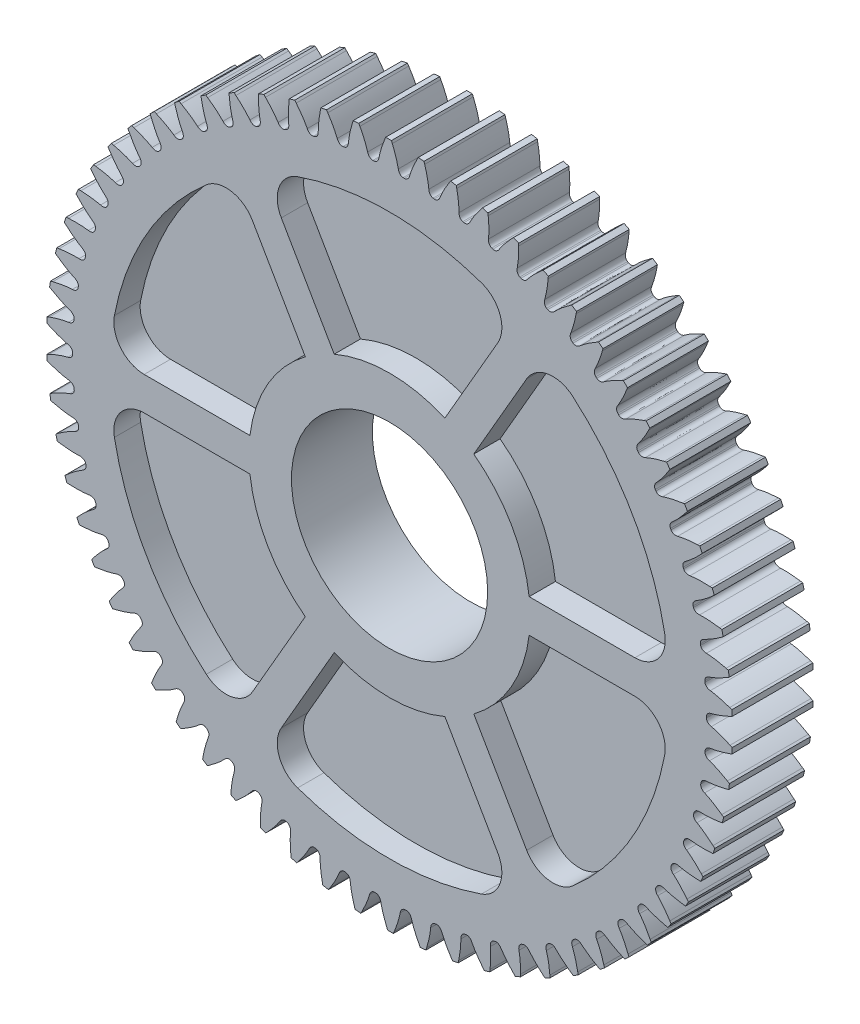
SolidWorks part; units mm, degrees
material "PA Тип 6"
ref_plane "Спереди" through (0, 0, 0) normal (0, 0, 1) x (1, 0, 0)
ref_plane "Сверху" through (0, 0, 0) normal (0, 1, 0) x (1, 0, 0)
ref_plane "Справа" through (0, 0, 0) normal (1, 0, 0) x (0, 0, -1)
sketch "Эскиз1" plane through (0, 0, 0) normal (0, 0, 1) x (1, 0, 0)
  line B0 (-1.4645, 16.7792) -> (-1.5192, 16.8818)
  line B1 (-0.2353, 16.8414) -> (-0.1912, 16.9489)
  line B2 (-3.0528, 16.564) -> (-3.117, 16.6609)
  line B3 (-1.8351, 16.7427) -> (-1.8014, 16.854)
  line B4 (-4.6135, 16.1988) -> (-4.6866, 16.2892)
  line B5 (-3.4183, 16.4925) -> (-3.3953, 16.6064)
  line B6 (-6.1324, 15.6869) -> (-6.2138, 15.77)
  line B7 (-4.9705, 16.0929) -> (-4.9585, 16.2085)
  line B8 (-7.5958, 15.033) -> (-7.6847, 15.1079)
  line B9 (-6.4777, 15.5475) -> (-6.4768, 15.6638)
  line B10 (-8.9904, 14.2429) -> (-9.086, 14.309)
  line B11 (-7.9263, 14.8614) -> (-7.9364, 14.9772)
  line B12 (-10.3035, 13.3238) -> (-10.405, 13.3805)
  line B13 (-9.303, 14.0407) -> (-9.3241, 14.155)
  line B14 (-11.5234, 12.2841) -> (-11.6298, 12.3309)
  line B15 (-10.5956, 13.0928) -> (-10.6274, 13.2046)
  line B16 (-12.6389, 11.1331) -> (-12.7492, 11.1696)
  line B17 (-11.7921, 12.0263) -> (-11.8345, 12.1346)
  line B18 (-13.6399, 9.8813) -> (-13.7532, 9.9071)
  line B19 (-12.8819, 10.8509) -> (-12.9343, 10.9547)
  line B20 (-14.5174, 8.54) -> (-14.6327, 8.5549)
  line B21 (-13.855, 9.5773) -> (-13.9171, 9.6756)
  line B22 (-15.2635, 7.1213) -> (-15.3796, 7.1253)
  line B23 (-14.7027, 8.2169) -> (-14.7738, 8.3089)
  line B24 (-15.8713, 5.6382) -> (-15.9873, 5.6311)
  line B25 (-15.4172, 6.7822) -> (-15.4967, 6.8669)
  line B26 (-16.3354, 4.104) -> (-16.4502, 4.0859)
  line B27 (-15.992, 5.286) -> (-16.0793, 5.3628)
  line B28 (-16.6515, 2.5326) -> (-16.7641, 2.5037)
  line B29 (-16.4221, 3.7419) -> (-16.5162, 3.8101)
  line B30 (-16.8168, 0.9383) -> (-16.9262, 0.8988)
  line B31 (-16.7034, 2.1639) -> (-16.8036, 2.2228)
  line B32 (-16.8299, -0.6644) -> (-16.9349, -0.7142)
  line B33 (-16.8335, 0.5664) -> (-16.9388, 0.6155)
  line B34 (-16.6905, -2.2612) -> (-16.7904, -2.3207)
  line B35 (-16.8111, -1.0363) -> (-16.9206, -0.9974)
  line B36 (-16.4, -3.8375) -> (-16.4938, -3.9062)
  line B37 (-16.6365, -2.6296) -> (-16.7492, -2.6013)
  line B38 (-15.961, -5.3791) -> (-16.0478, -5.4564)
  line B39 (-16.3112, -4.1991) -> (-16.4261, -4.1817)
  line B40 (-15.3774, -6.8719) -> (-15.4564, -6.9571)
  line B41 (-15.8382, -5.7306) -> (-15.9542, -5.7241)
  line B42 (-14.6545, -8.3025) -> (-14.7251, -8.3948)
  line B43 (-15.2217, -7.2101) -> (-15.3379, -7.2148)
  line B44 (-13.799, -9.6579) -> (-13.8605, -9.7565)
  line B45 (-14.4674, -8.6244) -> (-14.5826, -8.64)
  line B46 (-12.8185, -10.9258) -> (-12.8703, -11.0299)
  line B47 (-13.5821, -9.9606) -> (-13.6953, -9.9871)
  line B48 (-11.7218, -12.0948) -> (-11.7636, -12.2033)
  line B49 (-12.5738, -11.2065) -> (-12.6839, -11.2437)
  line B50 (-10.5191, -13.1543) -> (-10.5503, -13.2663)
  line B51 (-11.4516, -12.351) -> (-11.5577, -12.3985)
  line B52 (-9.2211, -14.0946) -> (-9.2415, -14.2091)
  line B53 (-10.2257, -13.3836) -> (-10.3268, -13.4409)
  line B54 (-7.8395, -14.9073) -> (-7.849, -15.0232)
  line B55 (-8.9072, -14.295) -> (-9.0024, -14.3617)
  line B56 (-6.387, -15.585) -> (-6.3854, -15.7013)
  line B57 (-7.5081, -15.077) -> (-7.5965, -15.1524)
  line B58 (-4.8766, -16.1216) -> (-4.864, -16.2371)
  line B59 (-6.0409, -15.7224) -> (-6.1218, -15.8059)
  line B60 (-3.3221, -16.5121) -> (-3.2985, -16.626)
  line B61 (-4.519, -16.2254) -> (-4.5916, -16.3162)
  line B62 (-1.7375, -16.7531) -> (-1.7032, -16.8642)
  line B63 (-2.9562, -16.5815) -> (-3.0199, -16.6788)
  line B64 (-0.1371, -16.8424) -> (-0.0924, -16.9497)
  line B65 (-1.3667, -16.7875) -> (-1.4208, -16.8904)
  line B66 (1.4645, -16.7792) -> (1.5192, -16.8818)
  line B67 (0.2353, -16.8414) -> (0.1912, -16.9489)
  line B68 (3.0528, -16.564) -> (3.117, -16.6609)
  line B69 (1.8351, -16.7427) -> (1.8014, -16.854)
  line B70 (4.6135, -16.1988) -> (4.6866, -16.2892)
  line B71 (3.4183, -16.4925) -> (3.3953, -16.6064)
  line B72 (6.1324, -15.6869) -> (6.2138, -15.77)
  line B73 (4.9705, -16.0929) -> (4.9585, -16.2085)
  line B74 (7.5958, -15.033) -> (7.6847, -15.1079)
  line B75 (6.4777, -15.5475) -> (6.4768, -15.6638)
  line B76 (8.9904, -14.2429) -> (9.086, -14.309)
  line B77 (7.9263, -14.8614) -> (7.9364, -14.9772)
  line B78 (10.3035, -13.3238) -> (10.405, -13.3805)
  line B79 (9.303, -14.0407) -> (9.3241, -14.155)
  line B80 (11.5234, -12.2841) -> (11.6298, -12.3309)
  line B81 (10.5956, -13.0928) -> (10.6274, -13.2046)
  line B82 (12.6389, -11.1331) -> (12.7492, -11.1696)
  line B83 (11.7921, -12.0263) -> (11.8345, -12.1346)
  line B84 (13.6399, -9.8813) -> (13.7532, -9.9071)
  line B85 (12.8819, -10.8509) -> (12.9343, -10.9547)
  line B86 (14.5174, -8.54) -> (14.6327, -8.5549)
  line B87 (13.855, -9.5773) -> (13.9171, -9.6756)
  line B88 (15.2635, -7.1213) -> (15.3796, -7.1253)
  line B89 (14.7027, -8.2169) -> (14.7738, -8.3089)
  line B90 (15.8713, -5.6382) -> (15.9873, -5.6311)
  line B91 (15.4172, -6.7822) -> (15.4967, -6.8669)
  line B92 (16.3354, -4.104) -> (16.4502, -4.0859)
  line B93 (15.992, -5.286) -> (16.0793, -5.3628)
  line B94 (16.6515, -2.5326) -> (16.7641, -2.5037)
  line B95 (16.4221, -3.7419) -> (16.5162, -3.8101)
  line B96 (16.8168, -0.9383) -> (16.9262, -0.8988)
  line B97 (16.7034, -2.1639) -> (16.8036, -2.2228)
  line B98 (16.8299, 0.6644) -> (16.9349, 0.7142)
  line B99 (16.8335, -0.5664) -> (16.9388, -0.6155)
  line B100 (16.6905, 2.2612) -> (16.7904, 2.3207)
  line B101 (16.8111, 1.0363) -> (16.9206, 0.9974)
  line B102 (16.4, 3.8375) -> (16.4938, 3.9062)
  line B103 (16.6365, 2.6296) -> (16.7492, 2.6013)
  line B104 (15.961, 5.3791) -> (16.0478, 5.4564)
  line B105 (16.3112, 4.1991) -> (16.4261, 4.1817)
  line B106 (15.3774, 6.8719) -> (15.4564, 6.9571)
  line B107 (15.8382, 5.7306) -> (15.9542, 5.7241)
  line B108 (14.6545, 8.3025) -> (14.7251, 8.3948)
  line B109 (15.2217, 7.2101) -> (15.3379, 7.2148)
  line B110 (13.799, 9.6579) -> (13.8605, 9.7565)
  line B111 (14.4674, 8.6244) -> (14.5826, 8.64)
  line B112 (12.8185, 10.9258) -> (12.8703, 11.0299)
  line B113 (13.5821, 9.9606) -> (13.6953, 9.9871)
  line B114 (11.7218, 12.0948) -> (11.7636, 12.2033)
  line B115 (12.5738, 11.2065) -> (12.6839, 11.2437)
  line B116 (10.5191, 13.1543) -> (10.5503, 13.2663)
  line B117 (11.4516, 12.351) -> (11.5577, 12.3985)
  line B118 (9.2211, 14.0946) -> (9.2415, 14.2091)
  line B119 (10.2257, 13.3836) -> (10.3268, 13.4409)
  line B120 (7.8395, 14.9073) -> (7.849, 15.0232)
  line B121 (8.9072, 14.295) -> (9.0024, 14.3617)
  line B122 (6.387, 15.585) -> (6.3854, 15.7013)
  line B123 (7.5081, 15.077) -> (7.5965, 15.1524)
  line B124 (4.8766, 16.1216) -> (4.864, 16.2371)
  line B125 (6.0409, 15.7224) -> (6.1218, 15.8059)
  line B126 (3.3221, 16.5121) -> (3.2985, 16.626)
  line B127 (4.519, 16.2254) -> (4.5916, 16.3162)
  line B128 (1.7375, 16.7531) -> (1.7032, 16.8642)
  line B129 (2.9562, 16.5815) -> (3.0199, 16.6788)
  line B130 (0.1371, 16.8424) -> (0.0924, 16.9497)
  line B131 (1.3667, 16.7875) -> (1.4208, 16.8904)
  arc B132 (-0.7605, 15.6469) -> (-0.8215, 15.6438) centre (0, 0) ccw
  arc B133 (-2.2444, 15.5037) -> (-2.3048, 15.4949) centre (0, 0) ccw
  arc B134 (-3.7079, 15.2202) -> (-3.7672, 15.2056) centre (0, 0) ccw
  arc B135 (-5.1379, 14.7988) -> (-5.1956, 14.7787) centre (0, 0) ccw
  arc B136 (-6.5213, 14.2434) -> (-6.5769, 14.2179) centre (0, 0) ccw
  arc B137 (-7.8457, 13.559) -> (-7.8986, 13.5283) centre (0, 0) ccw
  arc B138 (-9.0991, 12.7519) -> (-9.1488, 12.7163) centre (0, 0) ccw
  arc B139 (-10.27, 11.8292) -> (-10.3161, 11.789) centre (0, 0) ccw
  arc B140 (-11.348, 10.7994) -> (-11.39, 10.7551) centre (0, 0) ccw
  arc B141 (-12.3231, 9.6718) -> (-12.3607, 9.6237) centre (0, 0) ccw
  arc B142 (-13.1867, 8.4566) -> (-13.2196, 8.4051) centre (0, 0) ccw
  arc B143 (-13.9308, 7.1649) -> (-13.9587, 7.1105) centre (0, 0) ccw
  arc B144 (-14.5488, 5.8082) -> (-14.5714, 5.7514) centre (0, 0) ccw
  arc B145 (-15.035, 4.399) -> (-15.0521, 4.3403) centre (0, 0) ccw
  arc B146 (-15.3851, 2.9499) -> (-15.3965, 2.8898) centre (0, 0) ccw
  arc B147 (-15.5958, 1.4741) -> (-15.6015, 1.4132) centre (0, 0) ccw
  arc B148 (-15.6653, -0.0151) -> (-15.6652, -0.0762) centre (0, 0) ccw
  arc B149 (-15.593, -1.5041) -> (-15.587, -1.5649) centre (0, 0) ccw
  arc B150 (-15.3794, -2.9795) -> (-15.3676, -3.0395) centre (0, 0) ccw
  arc B151 (-15.0265, -4.4279) -> (-15.0091, -4.4865) centre (0, 0) ccw
  arc B152 (-14.5376, -5.8362) -> (-14.5147, -5.8929) centre (0, 0) ccw
  arc B153 (-13.917, -7.1917) -> (-13.8888, -7.2459) centre (0, 0) ccw
  arc B154 (-13.1704, -8.482) -> (-13.1372, -8.5333) centre (0, 0) ccw
  arc B155 (-12.3045, -9.6955) -> (-12.2665, -9.7435) centre (0, 0) ccw
  arc B156 (-11.3271, -10.8212) -> (-11.2848, -10.8653) centre (0, 0) ccw
  arc B157 (-10.2472, -11.849) -> (-10.2009, -11.8888) centre (0, 0) ccw
  arc B158 (-9.0745, -12.7694) -> (-9.0246, -12.8047) centre (0, 0) ccw
  arc B159 (-7.8196, -13.5741) -> (-7.7666, -13.6045) centre (0, 0) ccw
  arc B160 (-6.4939, -14.256) -> (-6.4382, -14.2812) centre (0, 0) ccw
  arc B161 (-5.1094, -14.8087) -> (-5.0516, -14.8285) centre (0, 0) ccw
  arc B162 (-3.6786, -15.2273) -> (-3.6192, -15.2415) centre (0, 0) ccw
  arc B163 (-2.2145, -15.508) -> (-2.154, -15.5166) centre (0, 0) ccw
  arc B164 (-0.7303, -15.6483) -> (-0.6693, -15.651) centre (0, 0) ccw
  arc B165 (0.7605, -15.6469) -> (0.8215, -15.6438) centre (0, 0) ccw
  arc B166 (2.2444, -15.5037) -> (2.3048, -15.4949) centre (0, 0) ccw
  arc B167 (3.7079, -15.2202) -> (3.7672, -15.2056) centre (0, 0) ccw
  arc B168 (5.1379, -14.7988) -> (5.1956, -14.7787) centre (0, 0) ccw
  arc B169 (6.5213, -14.2434) -> (6.5769, -14.2179) centre (0, 0) ccw
  arc B170 (7.8457, -13.559) -> (7.8986, -13.5283) centre (0, 0) ccw
  arc B171 (9.0991, -12.7519) -> (9.1488, -12.7163) centre (0, 0) ccw
  arc B172 (10.27, -11.8292) -> (10.3161, -11.789) centre (0, 0) ccw
  arc B173 (11.348, -10.7994) -> (11.39, -10.7551) centre (0, 0) ccw
  arc B174 (12.3231, -9.6718) -> (12.3607, -9.6237) centre (0, 0) ccw
  arc B175 (13.1867, -8.4566) -> (13.2196, -8.4051) centre (0, 0) ccw
  arc B176 (13.9308, -7.1649) -> (13.9587, -7.1105) centre (0, 0) ccw
  arc B177 (14.5488, -5.8082) -> (14.5714, -5.7514) centre (0, 0) ccw
  arc B178 (15.035, -4.399) -> (15.0521, -4.3403) centre (0, 0) ccw
  arc B179 (15.3851, -2.9499) -> (15.3965, -2.8898) centre (0, 0) ccw
  arc B180 (15.5958, -1.4741) -> (15.6015, -1.4132) centre (0, 0) ccw
  arc B181 (15.6653, 0.0151) -> (15.6652, 0.0762) centre (0, 0) ccw
  arc B182 (15.593, 1.5041) -> (15.587, 1.5649) centre (0, 0) ccw
  arc B183 (15.3794, 2.9795) -> (15.3676, 3.0395) centre (0, 0) ccw
  arc B184 (15.0265, 4.4279) -> (15.0091, 4.4865) centre (0, 0) ccw
  arc B185 (14.5376, 5.8362) -> (14.5147, 5.8929) centre (0, 0) ccw
  arc B186 (13.917, 7.1917) -> (13.8888, 7.2459) centre (0, 0) ccw
  arc B187 (13.1704, 8.482) -> (13.1372, 8.5333) centre (0, 0) ccw
  arc B188 (12.3045, 9.6955) -> (12.2665, 9.7435) centre (0, 0) ccw
  arc B189 (11.3271, 10.8212) -> (11.2848, 10.8653) centre (0, 0) ccw
  arc B190 (10.2472, 11.849) -> (10.2009, 11.8888) centre (0, 0) ccw
  arc B191 (9.0745, 12.7694) -> (9.0246, 12.8047) centre (0, 0) ccw
  arc B192 (7.8196, 13.5741) -> (7.7666, 13.6045) centre (0, 0) ccw
  arc B193 (6.4939, 14.256) -> (6.4382, 14.2812) centre (0, 0) ccw
  arc B194 (5.1094, 14.8087) -> (5.0516, 14.8285) centre (0, 0) ccw
  arc B195 (3.6786, 15.2273) -> (3.6192, 15.2415) centre (0, 0) ccw
  arc B196 (2.2145, 15.508) -> (2.154, 15.5166) centre (0, 0) ccw
  arc B197 (0.7303, 15.6483) -> (0.6693, 15.651) centre (0, 0) ccw
  arc B198 (-1.5192, 16.8818) -> (-1.8014, 16.854) centre (0, 0) ccw
  arc B199 (-3.117, 16.6609) -> (-3.3953, 16.6064) centre (0, 0) ccw
  arc B200 (-4.6866, 16.2892) -> (-4.9585, 16.2085) centre (0, 0) ccw
  arc B201 (-6.2138, 15.77) -> (-6.4768, 15.6638) centre (0, 0) ccw
  arc B202 (-7.6847, 15.1079) -> (-7.9364, 14.9772) centre (0, 0) ccw
  arc B203 (-9.086, 14.309) -> (-9.3241, 14.155) centre (0, 0) ccw
  arc B204 (-10.405, 13.3805) -> (-10.6274, 13.2046) centre (0, 0) ccw
  arc B205 (-11.6298, 12.3309) -> (-11.8345, 12.1346) centre (0, 0) ccw
  arc B206 (-12.7492, 11.1696) -> (-12.9343, 10.9547) centre (0, 0) ccw
  arc B207 (-13.7532, 9.9071) -> (-13.9171, 9.6756) centre (0, 0) ccw
  arc B208 (-14.6327, 8.5549) -> (-14.7738, 8.3089) centre (0, 0) ccw
  arc B209 (-15.3796, 7.1253) -> (-15.4967, 6.8669) centre (0, 0) ccw
  arc B210 (-15.9873, 5.6311) -> (-16.0793, 5.3628) centre (0, 0) ccw
  arc B211 (-16.4502, 4.0859) -> (-16.5162, 3.8101) centre (0, 0) ccw
  arc B212 (-16.7641, 2.5037) -> (-16.8036, 2.2228) centre (0, 0) ccw
  arc B213 (-16.9262, 0.8988) -> (-16.9388, 0.6155) centre (0, 0) ccw
  arc B214 (-16.9349, -0.7142) -> (-16.9206, -0.9974) centre (0, 0) ccw
  arc B215 (-16.7904, -2.3207) -> (-16.7492, -2.6013) centre (0, 0) ccw
  arc B216 (-16.4938, -3.9062) -> (-16.4261, -4.1817) centre (0, 0) ccw
  arc B217 (-16.0478, -5.4564) -> (-15.9542, -5.7241) centre (0, 0) ccw
  arc B218 (-15.4564, -6.9571) -> (-15.3379, -7.2148) centre (0, 0) ccw
  arc B219 (-14.7251, -8.3948) -> (-14.5826, -8.64) centre (0, 0) ccw
  arc B220 (-13.8605, -9.7565) -> (-13.6953, -9.9871) centre (0, 0) ccw
  arc B221 (-12.8703, -11.0299) -> (-12.6839, -11.2437) centre (0, 0) ccw
  arc B222 (-11.7636, -12.2033) -> (-11.5577, -12.3985) centre (0, 0) ccw
  arc B223 (-10.5503, -13.2663) -> (-10.3268, -13.4409) centre (0, 0) ccw
  arc B224 (-9.2415, -14.2091) -> (-9.0024, -14.3617) centre (0, 0) ccw
  arc B225 (-7.849, -15.0232) -> (-7.5965, -15.1524) centre (0, 0) ccw
  arc B226 (-6.3854, -15.7013) -> (-6.1218, -15.8059) centre (0, 0) ccw
  arc B227 (-4.864, -16.2371) -> (-4.5916, -16.3162) centre (0, 0) ccw
  arc B228 (-3.2985, -16.626) -> (-3.0199, -16.6788) centre (0, 0) ccw
  arc B229 (-1.7032, -16.8642) -> (-1.4208, -16.8904) centre (0, 0) ccw
  arc B230 (-0.0924, -16.9497) -> (0.1912, -16.9489) centre (0, 0) ccw
  arc B231 (1.5192, -16.8818) -> (1.8014, -16.854) centre (0, 0) ccw
  arc B232 (3.117, -16.6609) -> (3.3953, -16.6064) centre (0, 0) ccw
  arc B233 (4.6866, -16.2892) -> (4.9585, -16.2085) centre (0, 0) ccw
  arc B234 (6.2138, -15.77) -> (6.4768, -15.6638) centre (0, 0) ccw
  arc B235 (7.6847, -15.1079) -> (7.9364, -14.9772) centre (0, 0) ccw
  arc B236 (9.086, -14.309) -> (9.3241, -14.155) centre (0, 0) ccw
  arc B237 (10.405, -13.3805) -> (10.6274, -13.2046) centre (0, 0) ccw
  arc B238 (11.6298, -12.3309) -> (11.8345, -12.1346) centre (0, 0) ccw
  arc B239 (12.7492, -11.1696) -> (12.9343, -10.9547) centre (0, 0) ccw
  arc B240 (13.7532, -9.9071) -> (13.9171, -9.6756) centre (0, 0) ccw
  arc B241 (14.6327, -8.5549) -> (14.7738, -8.3089) centre (0, 0) ccw
  arc B242 (15.3796, -7.1253) -> (15.4967, -6.8669) centre (0, 0) ccw
  arc B243 (15.9873, -5.6311) -> (16.0793, -5.3628) centre (0, 0) ccw
  arc B244 (16.4502, -4.0859) -> (16.5162, -3.8101) centre (0, 0) ccw
  arc B245 (16.7641, -2.5037) -> (16.8036, -2.2228) centre (0, 0) ccw
  arc B246 (16.9262, -0.8988) -> (16.9388, -0.6155) centre (0, 0) ccw
  arc B247 (16.9349, 0.7142) -> (16.9206, 0.9974) centre (0, 0) ccw
  arc B248 (16.7904, 2.3207) -> (16.7492, 2.6013) centre (0, 0) ccw
  arc B249 (16.4938, 3.9062) -> (16.4261, 4.1817) centre (0, 0) ccw
  arc B250 (16.0478, 5.4564) -> (15.9542, 5.7241) centre (0, 0) ccw
  arc B251 (15.4564, 6.9571) -> (15.3379, 7.2148) centre (0, 0) ccw
  arc B252 (14.7251, 8.3948) -> (14.5826, 8.64) centre (0, 0) ccw
  arc B253 (13.8605, 9.7565) -> (13.6953, 9.9871) centre (0, 0) ccw
  arc B254 (12.8703, 11.0299) -> (12.6839, 11.2437) centre (0, 0) ccw
  arc B255 (11.7636, 12.2033) -> (11.5577, 12.3985) centre (0, 0) ccw
  arc B256 (10.5503, 13.2663) -> (10.3268, 13.4409) centre (0, 0) ccw
  arc B257 (9.2415, 14.2091) -> (9.0024, 14.3617) centre (0, 0) ccw
  arc B258 (7.849, 15.0232) -> (7.5965, 15.1524) centre (0, 0) ccw
  arc B259 (6.3854, 15.7013) -> (6.1218, 15.8059) centre (0, 0) ccw
  arc B260 (4.864, 16.2371) -> (4.5916, 16.3162) centre (0, 0) ccw
  arc B261 (3.2985, 16.626) -> (3.0199, 16.6788) centre (0, 0) ccw
  arc B262 (1.7032, 16.8642) -> (1.4208, 16.8904) centre (0, 0) ccw
  arc B263 (0.0924, 16.9497) -> (-0.1912, 16.9489) centre (0, 0) ccw
  spline B264 degree 3 poles (-0.5258, 15.9016) (-0.5329, 15.8486) (-0.55, 15.8015) (-0.5772, 15.7603) (-0.5924, 15.7373) (-0.6106, 15.7143) (-0.632, 15.697) (-0.6503, 15.6822) (-0.6718, 15.6693) (-0.6938, 15.6609) (-0.7147, 15.653) (-0.737, 15.6483) (-0.7605, 15.6469) knots 0 0 0 0 1 1 1 2 2 2 3 3 3 4 4 4 4
  spline B265 degree 3 poles (-0.5258, 15.9016) (-0.51, 15.9804) (-0.4922, 16.0588) (-0.4722, 16.1365) (-0.452, 16.2155) (-0.4292, 16.2938) (-0.405, 16.3716) (-0.3804, 16.4505) (-0.3537, 16.5289) (-0.3256, 16.6066) (-0.2972, 16.6855) (-0.2671, 16.7637) (-0.2353, 16.8414) knots 0 0 0 0 1 1 1 2 2 2 3 3 3 4 4 4 4
  spline B266 degree 3 poles (-1.0806, 15.8735) (-1.0682, 15.8215) (-1.0464, 15.7764) (-1.0152, 15.7381) (-0.9978, 15.7168) (-0.9774, 15.6957) (-0.9543, 15.6807) (-0.9346, 15.6678) (-0.912, 15.6572) (-0.8893, 15.6511) (-0.8676, 15.6452) (-0.845, 15.6428) (-0.8215, 15.6438) knots 0 0 0 0 1 1 1 2 2 2 3 3 3 4 4 4 4
  spline B267 degree 3 poles (-1.0806, 15.8735) (-1.1043, 15.9504) (-1.1299, 16.0265) (-1.1576, 16.1019) (-1.1858, 16.1784) (-1.2163, 16.254) (-1.2483, 16.329) (-1.2807, 16.405) (-1.3151, 16.4803) (-1.3509, 16.5548) (-1.3872, 16.6304) (-1.425, 16.7052) (-1.4645, 16.7792) knots 0 0 0 0 1 1 1 2 2 2 3 3 3 4 4 4 4
  spline B268 degree 3 poles (-2.035, 15.7796) (-2.037, 15.7261) (-2.0496, 15.6776) (-2.0727, 15.634) (-2.0856, 15.6098) (-2.1016, 15.5851) (-2.1213, 15.5658) (-2.1381, 15.5494) (-2.1582, 15.5345) (-2.1793, 15.5241) (-2.1994, 15.5141) (-2.2211, 15.5074) (-2.2444, 15.5037) knots 0 0 0 0 1 1 1 2 2 2 3 3 3 4 4 4 4
  spline B269 degree 3 poles (-2.035, 15.7796) (-2.0268, 15.8596) (-2.0164, 15.9393) (-2.004, 16.0186) (-1.9913, 16.0991) (-1.9761, 16.1793) (-1.9594, 16.259) (-1.9424, 16.3399) (-1.9233, 16.4204) (-1.9027, 16.5005) (-1.8819, 16.5817) (-1.8593, 16.6624) (-1.8351, 16.7427) knots 0 0 0 0 1 1 1 2 2 2 3 3 3 4 4 4 4
  spline B270 degree 3 poles (-2.5846, 15.6989) (-2.5673, 15.6483) (-2.5413, 15.6055) (-2.5066, 15.5704) (-2.4873, 15.5508) (-2.4649, 15.5318) (-2.4405, 15.519) (-2.4197, 15.508) (-2.3962, 15.4996) (-2.373, 15.4957) (-2.3508, 15.4919) (-2.3281, 15.4916) (-2.3048, 15.4949) knots 0 0 0 0 1 1 1 2 2 2 3 3 3 4 4 4 4
  spline B271 degree 3 poles (-2.5846, 15.6989) (-2.6155, 15.7732) (-2.6482, 15.8465) (-2.683, 15.9189) (-2.7182, 15.9924) (-2.7558, 16.0648) (-2.7948, 16.1364) (-2.8343, 16.209) (-2.8757, 16.2806) (-2.9184, 16.3514) (-2.9617, 16.4232) (-3.0065, 16.4941) (-3.0528, 16.564) knots 0 0 0 0 1 1 1 2 2 2 3 3 3 4 4 4 4
  spline B272 degree 3 poles (-3.5257, 15.5147) (-3.5226, 15.4613) (-3.5305, 15.4118) (-3.5495, 15.3662) (-3.56, 15.3408) (-3.5735, 15.3148) (-3.5913, 15.2937) (-3.6064, 15.2757) (-3.6251, 15.259) (-3.6451, 15.2466) (-3.6642, 15.2348) (-3.6851, 15.226) (-3.7079, 15.2202) knots 0 0 0 0 1 1 1 2 2 2 3 3 3 4 4 4 4
  spline B273 degree 3 poles (-3.5257, 15.5147) (-3.5252, 15.5951) (-3.5224, 15.6754) (-3.5176, 15.7556) (-3.5126, 15.8369) (-3.5051, 15.9182) (-3.496, 15.9991) (-3.4868, 16.0813) (-3.4754, 16.1632) (-3.4626, 16.2449) (-3.4496, 16.3277) (-3.4348, 16.4102) (-3.4183, 16.4925) knots 0 0 0 0 1 1 1 2 2 2 3 3 3 4 4 4 4
  spline B274 degree 3 poles (-4.0652, 15.3822) (-4.0432, 15.3334) (-4.0132, 15.2932) (-3.9753, 15.2616) (-3.9542, 15.244) (-3.9301, 15.2271) (-3.9047, 15.2167) (-3.8829, 15.2078) (-3.8586, 15.2016) (-3.8352, 15.1999) (-3.8128, 15.1983) (-3.7902, 15.2002) (-3.7672, 15.2056) knots 0 0 0 0 1 1 1 2 2 2 3 3 3 4 4 4 4
  spline B275 degree 3 poles (-4.0652, 15.3822) (-4.1029, 15.4532) (-4.1426, 15.5231) (-4.184, 15.5918) (-4.2261, 15.6616) (-4.2704, 15.7301) (-4.316, 15.7977) (-4.3622, 15.8662) (-4.4103, 15.9336) (-4.4595, 16) (-4.5094, 16.0673) (-4.5607, 16.1336) (-4.6135, 16.1988) knots 0 0 0 0 1 1 1 2 2 2 3 3 3 4 4 4 4
  spline B276 degree 3 poles (-4.9845, 15.1093) (-4.9764, 15.0565) (-4.9795, 15.0064) (-4.994, 14.9592) (-5.0021, 14.933) (-5.0131, 14.9057) (-5.0288, 14.8831) (-5.0422, 14.8638) (-5.0591, 14.8453) (-5.0779, 14.8311) (-5.0957, 14.8175) (-5.1157, 14.8068) (-5.1379, 14.7988) knots 0 0 0 0 1 1 1 2 2 2 3 3 3 4 4 4 4
  spline B277 degree 3 poles (-4.9845, 15.1093) (-4.9916, 15.1894) (-4.9965, 15.2696) (-4.9993, 15.3499) (-5.0021, 15.4313) (-5.0023, 15.5129) (-5.001, 15.5944) (-4.9996, 15.677) (-4.9961, 15.7597) (-4.9911, 15.8422) (-4.986, 15.9259) (-4.9791, 16.0094) (-4.9705, 16.0929) knots 0 0 0 0 1 1 1 2 2 2 3 3 3 4 4 4 4
  spline B278 degree 3 poles (-5.509, 14.9261) (-5.4824, 14.8797) (-5.4488, 14.8425) (-5.408, 14.8146) (-5.3854, 14.7991) (-5.3598, 14.7846) (-5.3334, 14.7766) (-5.3109, 14.7699) (-5.2862, 14.766) (-5.2626, 14.7665) (-5.2402, 14.7671) (-5.2179, 14.7711) (-5.1956, 14.7787) knots 0 0 0 0 1 1 1 2 2 2 3 3 3 4 4 4 4
  spline B279 degree 3 poles (-5.509, 14.9261) (-5.5533, 14.9932) (-5.5994, 15.059) (-5.6472, 15.1235) (-5.6957, 15.189) (-5.7463, 15.253) (-5.7981, 15.3159) (-5.8506, 15.3797) (-5.9049, 15.4422) (-5.9602, 15.5036) (-6.0163, 15.5659) (-6.0737, 15.627) (-6.1324, 15.6869) knots 0 0 0 0 1 1 1 2 2 2 3 3 3 4 4 4 4
  spline B280 degree 3 poles (-6.3982, 14.5671) (-6.385, 14.5152) (-6.3834, 14.4651) (-6.3934, 14.4168) (-6.3989, 14.3899) (-6.4073, 14.3617) (-6.4207, 14.3377) (-6.4322, 14.3172) (-6.4474, 14.2972) (-6.4647, 14.2813) (-6.4812, 14.2661) (-6.5, 14.2534) (-6.5213, 14.2434) knots 0 0 0 0 1 1 1 2 2 2 3 3 3 4 4 4 4
  spline B281 degree 3 poles (-6.3982, 14.5671) (-6.4128, 14.6462) (-6.4254, 14.7255) (-6.4358, 14.8051) (-6.4463, 14.8859) (-6.4543, 14.9672) (-6.4607, 15.0484) (-6.4672, 15.1308) (-6.4715, 15.2134) (-6.4744, 15.296) (-6.4773, 15.3798) (-6.4784, 15.4636) (-6.4777, 15.5475) knots 0 0 0 0 1 1 1 2 2 2 3 3 3 4 4 4 4
  spline B282 degree 3 poles (-6.9028, 14.3348) (-6.872, 14.2911) (-6.835, 14.2574) (-6.7918, 14.2335) (-6.7677, 14.2202) (-6.7409, 14.2082) (-6.7139, 14.2028) (-6.6908, 14.1981) (-6.6658, 14.1967) (-6.6425, 14.1994) (-6.6202, 14.2021) (-6.5983, 14.2082) (-6.5769, 14.2179) knots 0 0 0 0 1 1 1 2 2 2 3 3 3 4 4 4 4
  spline B283 degree 3 poles (-6.9028, 14.3348) (-6.9533, 14.3974) (-7.0055, 14.4586) (-7.0592, 14.5182) (-7.1137, 14.5788) (-7.1702, 14.6377) (-7.2277, 14.6954) (-7.2861, 14.7539) (-7.346, 14.811) (-7.4069, 14.8669) (-7.4687, 14.9235) (-7.5316, 14.9789) (-7.5958, 15.033) knots 0 0 0 0 1 1 1 2 2 2 3 3 3 4 4 4 4
  spline B284 degree 3 poles (-7.7539, 13.893) (-7.7359, 13.8426) (-7.7295, 13.7929) (-7.7348, 13.7438) (-7.7378, 13.7165) (-7.7434, 13.6876) (-7.7545, 13.6624) (-7.764, 13.6409) (-7.7772, 13.6196) (-7.7929, 13.6021) (-7.8079, 13.5854) (-7.8255, 13.571) (-7.8457, 13.559) knots 0 0 0 0 1 1 1 2 2 2 3 3 3 4 4 4 4
  spline B285 degree 3 poles (-7.7539, 13.893) (-7.776, 13.9703) (-7.796, 14.0481) (-7.8139, 14.1264) (-7.8321, 14.2058) (-7.8478, 14.2859) (-7.8619, 14.3661) (-7.8762, 14.4475) (-7.8884, 14.5294) (-7.899, 14.6113) (-7.9099, 14.6945) (-7.9189, 14.7778) (-7.9263, 14.8614) knots 0 0 0 0 1 1 1 2 2 2 3 3 3 4 4 4 4
  spline B286 degree 3 poles (-8.2342, 13.6138) (-8.1993, 13.5732) (-8.1593, 13.5431) (-8.114, 13.5234) (-8.0888, 13.5125) (-8.0609, 13.5031) (-8.0335, 13.5003) (-8.0102, 13.4978) (-7.9851, 13.4988) (-7.9621, 13.5037) (-7.9402, 13.5085) (-7.919, 13.5167) (-7.8986, 13.5283) knots 0 0 0 0 1 1 1 2 2 2 3 3 3 4 4 4 4
  spline B287 degree 3 poles (-8.2342, 13.6138) (-8.2904, 13.6713) (-8.3481, 13.7272) (-8.4073, 13.7815) (-8.4673, 13.8366) (-8.5291, 13.8898) (-8.5919, 13.9418) (-8.6555, 13.9945) (-8.7206, 14.0456) (-8.7866, 14.0955) (-8.8534, 14.146) (-8.9214, 14.1952) (-8.9904, 14.2429) knots 0 0 0 0 1 1 1 2 2 2 3 3 3 4 4 4 4
  spline B288 degree 3 poles (-9.0394, 13.093) (-9.0167, 13.0446) (-9.0056, 12.9957) (-9.0063, 12.9463) (-9.0066, 12.9188) (-9.0095, 12.8896) (-9.0181, 12.8634) (-9.0255, 12.8411) (-9.0366, 12.8187) (-9.0506, 12.7997) (-9.0639, 12.7817) (-9.0801, 12.7657) (-9.0991, 12.7519) knots 0 0 0 0 1 1 1 2 2 2 3 3 3 4 4 4 4
  spline B289 degree 3 poles (-9.0394, 13.093) (-9.0688, 13.1679) (-9.0961, 13.2434) (-9.1213, 13.3196) (-9.147, 13.397) (-9.1702, 13.4752) (-9.1919, 13.5537) (-9.2138, 13.6334) (-9.2338, 13.7137) (-9.2522, 13.7943) (-9.2709, 13.876) (-9.2878, 13.9582) (-9.303, 14.0407) knots 0 0 0 0 1 1 1 2 2 2 3 3 3 4 4 4 4
  spline B290 degree 3 poles (-9.491, 12.7694) (-9.4524, 12.7324) (-9.4097, 12.7062) (-9.3627, 12.6909) (-9.3366, 12.6824) (-9.308, 12.6757) (-9.2804, 12.6755) (-9.2569, 12.6753) (-9.2321, 12.6786) (-9.2097, 12.6857) (-9.1883, 12.6925) (-9.168, 12.7027) (-9.1488, 12.7163) knots 0 0 0 0 1 1 1 2 2 2 3 3 3 4 4 4 4
  spline B291 degree 3 poles (-9.491, 12.7694) (-9.5524, 12.8213) (-9.6152, 12.8715) (-9.6792, 12.9199) (-9.7442, 12.969) (-9.8108, 13.0162) (-9.8782, 13.062) (-9.9466, 13.1084) (-10.0163, 13.1531) (-10.0866, 13.1964) (-10.158, 13.2404) (-10.2303, 13.2829) (-10.3035, 13.3238) knots 0 0 0 0 1 1 1 2 2 2 3 3 3 4 4 4 4
  spline B292 degree 3 poles (-10.243, 12.1745) (-10.2158, 12.1284) (-10.2002, 12.0808) (-10.1961, 12.0316) (-10.1938, 12.0042) (-10.1939, 11.9748) (-10.2, 11.948) (-10.2053, 11.925) (-10.2142, 11.9016) (-10.2263, 11.8815) (-10.2378, 11.8622) (-10.2524, 11.8448) (-10.27, 11.8292) knots 0 0 0 0 1 1 1 2 2 2 3 3 3 4 4 4 4
  spline B293 degree 3 poles (-10.243, 12.1745) (-10.2794, 12.2462) (-10.3138, 12.3188) (-10.3461, 12.3923) (-10.379, 12.4668) (-10.4096, 12.5425) (-10.4386, 12.6186) (-10.4681, 12.6959) (-10.4955, 12.7739) (-10.5215, 12.8524) (-10.5479, 12.932) (-10.5726, 13.0121) (-10.5956, 13.0928) knots 0 0 0 0 1 1 1 2 2 2 3 3 3 4 4 4 4
  spline B294 degree 3 poles (-10.6618, 11.8094) (-10.6199, 11.7762) (-10.5749, 11.7542) (-10.5267, 11.7434) (-10.4999, 11.7375) (-10.4707, 11.7335) (-10.4433, 11.7359) (-10.4199, 11.738) (-10.3955, 11.7436) (-10.3738, 11.7529) (-10.3532, 11.7617) (-10.334, 11.7737) (-10.3161, 11.789) knots 0 0 0 0 1 1 1 2 2 2 3 3 3 4 4 4 4
  spline B295 degree 3 poles (-10.6618, 11.8094) (-10.7279, 11.8553) (-10.7951, 11.8992) (-10.8635, 11.9413) (-10.9329, 11.9841) (-11.0037, 12.0247) (-11.0751, 12.0638) (-11.1476, 12.1036) (-11.2212, 12.1414) (-11.2954, 12.1779) (-11.3706, 12.2149) (-11.4466, 12.2503) (-11.5234, 12.2841) knots 0 0 0 0 1 1 1 2 2 2 3 3 3 4 4 4 4
  spline B296 degree 3 poles (-11.3539, 11.1457) (-11.3224, 11.1024) (-11.3023, 11.0565) (-11.2936, 11.0079) (-11.2887, 10.9809) (-11.286, 10.9516) (-11.2896, 10.9243) (-11.2926, 10.901) (-11.2993, 10.8768) (-11.3094, 10.8556) (-11.3191, 10.8354) (-11.3319, 10.8166) (-11.348, 10.7994) knots 0 0 0 0 1 1 1 2 2 2 3 3 3 4 4 4 4
  spline B297 degree 3 poles (-11.3539, 11.1457) (-11.3969, 11.2136) (-11.438, 11.2826) (-11.4773, 11.3527) (-11.5171, 11.4238) (-11.5547, 11.4962) (-11.5908, 11.5692) (-11.6275, 11.6433) (-11.6622, 11.7184) (-11.6956, 11.7941) (-11.7294, 11.8708) (-11.7616, 11.9482) (-11.7921, 12.0263) knots 0 0 0 0 1 1 1 2 2 2 3 3 3 4 4 4 4
  spline B298 degree 3 poles (-11.7361, 10.7425) (-11.6912, 10.7134) (-11.6443, 10.6958) (-11.5953, 10.6896) (-11.568, 10.6862) (-11.5387, 10.6851) (-11.5116, 10.6901) (-11.4885, 10.6944) (-11.4647, 10.7023) (-11.4441, 10.7135) (-11.4244, 10.7243) (-11.4063, 10.7381) (-11.39, 10.7551) knots 0 0 0 0 1 1 1 2 2 2 3 3 3 4 4 4 4
  spline B299 degree 3 poles (-11.7361, 10.7425) (-11.8062, 10.7818) (-11.8773, 10.8192) (-11.9494, 10.8546) (-12.0225, 10.8906) (-12.0969, 10.9243) (-12.1717, 10.9565) (-12.2476, 10.9891) (-12.3245, 11.0198) (-12.4018, 11.0491) (-12.4802, 11.0787) (-12.5592, 11.1067) (-12.6389, 11.1331) knots 0 0 0 0 1 1 1 2 2 2 3 3 3 4 4 4 4
  spline B300 degree 3 poles (-12.3619, 10.0159) (-12.3265, 9.9759) (-12.3021, 9.9321) (-12.2888, 9.8845) (-12.2814, 9.8581) (-12.2759, 9.8292) (-12.2769, 9.8017) (-12.2777, 9.7782) (-12.282, 9.7535) (-12.2901, 9.7314) (-12.2978, 9.7103) (-12.3088, 9.6905) (-12.3231, 9.6718) knots 0 0 0 0 1 1 1 2 2 2 3 3 3 4 4 4 4
  spline B301 degree 3 poles (-12.3619, 10.0159) (-12.4112, 10.0795) (-12.4587, 10.1443) (-12.5044, 10.2103) (-12.5508, 10.2773) (-12.5951, 10.3458) (-12.6381, 10.4151) (-12.6816, 10.4853) (-12.7233, 10.5568) (-12.7637, 10.6289) (-12.8047, 10.7021) (-12.8441, 10.7761) (-12.8819, 10.8509) knots 0 0 0 0 1 1 1 2 2 2 3 3 3 4 4 4 4
  spline B302 degree 3 poles (-12.7041, 9.5783) (-12.6566, 9.5536) (-12.6083, 9.5405) (-12.5589, 9.539) (-12.5314, 9.5382) (-12.5021, 9.5399) (-12.4756, 9.5474) (-12.453, 9.5539) (-12.4301, 9.5641) (-12.4106, 9.5772) (-12.392, 9.5898) (-12.3754, 9.6052) (-12.3607, 9.6237) knots 0 0 0 0 1 1 1 2 2 2 3 3 3 4 4 4 4
  spline B303 degree 3 poles (-12.7041, 9.5783) (-12.7777, 9.6107) (-12.852, 9.6412) (-12.9271, 9.6696) (-13.0033, 9.6984) (-13.0805, 9.7249) (-13.1581, 9.7498) (-13.2368, 9.7751) (-13.3162, 9.7984) (-13.3959, 9.8202) (-13.4768, 9.8422) (-13.5581, 9.8626) (-13.6399, 9.8813) knots 0 0 0 0 1 1 1 2 2 2 3 3 3 4 4 4 4
  spline B304 degree 3 poles (-13.258, 8.7955) (-13.219, 8.759) (-13.1905, 8.7177) (-13.1728, 8.6716) (-13.1629, 8.646) (-13.1547, 8.6178) (-13.153, 8.5903) (-13.1516, 8.5668) (-13.1535, 8.5419) (-13.1595, 8.5191) (-13.1651, 8.4974) (-13.1742, 8.4766) (-13.1867, 8.4566) knots 0 0 0 0 1 1 1 2 2 2 3 3 3 4 4 4 4
  spline B305 degree 3 poles (-13.258, 8.7955) (-13.3131, 8.8541) (-13.3666, 8.9141) (-13.4184, 8.9755) (-13.4709, 9.0377) (-13.5215, 9.1017) (-13.5708, 9.1666) (-13.6209, 9.2324) (-13.6692, 9.2996) (-13.7163, 9.3675) (-13.764, 9.4364) (-13.8102, 9.5064) (-13.855, 9.5773) knots 0 0 0 0 1 1 1 2 2 2 3 3 3 4 4 4 4
  spline B306 degree 3 poles (-13.557, 8.3273) (-13.5075, 8.3072) (-13.458, 8.2988) (-13.4088, 8.302) (-13.3814, 8.3039) (-13.3523, 8.3083) (-13.3267, 8.3183) (-13.3048, 8.3269) (-13.283, 8.3392) (-13.2648, 8.3541) (-13.2475, 8.3684) (-13.2324, 8.3854) (-13.2196, 8.4051) knots 0 0 0 0 1 1 1 2 2 2 3 3 3 4 4 4 4
  spline B307 degree 3 poles (-13.557, 8.3273) (-13.6334, 8.3526) (-13.7103, 8.3759) (-13.7877, 8.397) (-13.8663, 8.4185) (-13.9457, 8.4375) (-14.0253, 8.4549) (-14.106, 8.4726) (-14.1873, 8.4882) (-14.2687, 8.5023) (-14.3513, 8.5166) (-14.4342, 8.5292) (-14.5174, 8.54) knots 0 0 0 0 1 1 1 2 2 2 3 3 3 4 4 4 4
  spline B308 degree 3 poles (-14.0341, 7.4954) (-13.9917, 7.4628) (-13.9595, 7.4244) (-13.9374, 7.3802) (-13.9251, 7.3557) (-13.9143, 7.3283) (-13.91, 7.3011) (-13.9063, 7.2779) (-13.9059, 7.2529) (-13.9097, 7.2296) (-13.9132, 7.2075) (-13.9203, 7.1859) (-13.9308, 7.1649) knots 0 0 0 0 1 1 1 2 2 2 3 3 3 4 4 4 4
  spline B309 degree 3 poles (-14.0341, 7.4954) (-14.0945, 7.5485) (-14.1534, 7.6031) (-14.2108, 7.6593) (-14.269, 7.7163) (-14.3255, 7.7752) (-14.3807, 7.8351) (-14.4368, 7.8958) (-14.4913, 7.9581) (-14.5446, 8.0213) (-14.5986, 8.0854) (-14.6513, 8.1506) (-14.7027, 8.2169) knots 0 0 0 0 1 1 1 2 2 2 3 3 3 4 4 4 4
  spline B310 degree 3 poles (-14.2872, 7.0009) (-14.2359, 6.9856) (-14.186, 6.9819) (-14.1372, 6.9899) (-14.1101, 6.9943) (-14.0816, 7.0014) (-14.057, 7.0139) (-14.0361, 7.0245) (-14.0155, 7.0388) (-13.9988, 7.0554) (-13.983, 7.0712) (-13.9696, 7.0896) (-13.9587, 7.1105) knots 0 0 0 0 1 1 1 2 2 2 3 3 3 4 4 4 4
  spline B311 degree 3 poles (-14.2872, 7.0009) (-14.3656, 7.0189) (-14.4443, 7.0347) (-14.5235, 7.0484) (-14.6038, 7.0623) (-14.6846, 7.0737) (-14.7655, 7.0835) (-14.8475, 7.0934) (-14.9299, 7.1012) (-15.0123, 7.1075) (-15.0959, 7.1139) (-15.1796, 7.1185) (-15.2635, 7.1213) knots 0 0 0 0 1 1 1 2 2 2 3 3 3 4 4 4 4
  spline B312 degree 3 poles (-14.683, 6.1275) (-14.6377, 6.099) (-14.602, 6.0638) (-14.5758, 6.022) (-14.5613, 5.9987) (-14.5479, 5.9725) (-14.541, 5.9458) (-14.5352, 5.9231) (-14.5324, 5.8982) (-14.5339, 5.8747) (-14.5353, 5.8523) (-14.5403, 5.8302) (-14.5488, 5.8082) knots 0 0 0 0 1 1 1 2 2 2 3 3 3 4 4 4 4
  spline B313 degree 3 poles (-14.683, 6.1275) (-14.7482, 6.1746) (-14.812, 6.2233) (-14.8745, 6.2738) (-14.9379, 6.325) (-14.9997, 6.3783) (-15.0604, 6.4326) (-15.122, 6.4878) (-15.1821, 6.5446) (-15.2412, 6.6024) (-15.3011, 6.6611) (-15.3598, 6.721) (-15.4172, 6.7822) knots 0 0 0 0 1 1 1 2 2 2 3 3 3 4 4 4 4
  spline B314 degree 3 poles (-14.888, 5.6111) (-14.8355, 5.6008) (-14.7854, 5.6019) (-14.7376, 5.6144) (-14.7111, 5.6214) (-14.6834, 5.6312) (-14.6601, 5.6459) (-14.6402, 5.6585) (-14.6211, 5.6747) (-14.6061, 5.6928) (-14.5918, 5.7101) (-14.5802, 5.7296) (-14.5714, 5.7514) knots 0 0 0 0 1 1 1 2 2 2 3 3 3 4 4 4 4
  spline B315 degree 3 poles (-14.888, 5.6111) (-14.9677, 5.6216) (-15.0476, 5.6298) (-15.1277, 5.6359) (-15.2089, 5.6421) (-15.2905, 5.6458) (-15.3719, 5.6479) (-15.4545, 5.65) (-15.5373, 5.6499) (-15.6199, 5.6483) (-15.7038, 5.6467) (-15.7875, 5.6433) (-15.8713, 5.6382) knots 0 0 0 0 1 1 1 2 2 2 3 3 3 4 4 4 4
  spline B316 degree 3 poles (-15.199, 4.704) (-15.1512, 4.68) (-15.1123, 4.6484) (-15.0823, 4.6092) (-15.0656, 4.5874) (-15.0497, 4.5626) (-15.0404, 4.5367) (-15.0324, 4.5146) (-15.0272, 4.4901) (-15.0265, 4.4666) (-15.0258, 4.4442) (-15.0287, 4.4216) (-15.035, 4.399) knots 0 0 0 0 1 1 1 2 2 2 3 3 3 4 4 4 4
  spline B317 degree 3 poles (-15.199, 4.704) (-15.2684, 4.7447) (-15.3365, 4.7872) (-15.4035, 4.8315) (-15.4715, 4.8764) (-15.5381, 4.9236) (-15.6037, 4.9719) (-15.6702, 5.021) (-15.7355, 5.0718) (-15.7998, 5.1238) (-15.865, 5.1764) (-15.9291, 5.2305) (-15.992, 5.286) knots 0 0 0 0 1 1 1 2 2 2 3 3 3 4 4 4 4
  spline B318 degree 3 poles (-15.3539, 4.1705) (-15.3007, 4.1652) (-15.2509, 4.1711) (-15.2046, 4.1881) (-15.1788, 4.1975) (-15.1522, 4.21) (-15.1304, 4.2268) (-15.1118, 4.2412) (-15.0943, 4.2591) (-15.0811, 4.2786) (-15.0685, 4.2972) (-15.0588, 4.3177) (-15.0521, 4.3403) knots 0 0 0 0 1 1 1 2 2 2 3 3 3 4 4 4 4
  spline B319 degree 3 poles (-15.3539, 4.1705) (-15.4343, 4.1733) (-15.5146, 4.174) (-15.5949, 4.1724) (-15.6764, 4.1709) (-15.7579, 4.1668) (-15.8392, 4.1611) (-15.9216, 4.1553) (-16.004, 4.1474) (-16.0861, 4.138) (-16.1694, 4.1284) (-16.2525, 4.1171) (-16.3354, 4.104) knots 0 0 0 0 1 1 1 2 2 2 3 3 3 4 4 4 4
  spline B320 degree 3 poles (-15.5773, 3.238) (-15.5275, 3.2186) (-15.4857, 3.1908) (-15.4521, 3.1547) (-15.4334, 3.1345) (-15.4153, 3.1114) (-15.4035, 3.0865) (-15.3935, 3.0652) (-15.386, 3.0413) (-15.383, 3.018) (-15.3802, 2.9957) (-15.3809, 2.973) (-15.3851, 2.9499) knots 0 0 0 0 1 1 1 2 2 2 3 3 3 4 4 4 4
  spline B321 degree 3 poles (-15.5773, 3.238) (-15.6502, 3.2719) (-15.7221, 3.3077) (-15.793, 3.3454) (-15.8649, 3.3837) (-15.9357, 3.4243) (-16.0056, 3.4662) (-16.0765, 3.5087) (-16.1463, 3.5531) (-16.2153, 3.5987) (-16.2852, 3.6449) (-16.3541, 3.6927) (-16.4221, 3.7419) knots 0 0 0 0 1 1 1 2 2 2 3 3 3 4 4 4 4
  spline B322 degree 3 poles (-15.6809, 2.6921) (-15.6274, 2.6919) (-15.5784, 2.7025) (-15.5338, 2.7238) (-15.5091, 2.7357) (-15.4837, 2.7506) (-15.4637, 2.7694) (-15.4465, 2.7855) (-15.4308, 2.8051) (-15.4195, 2.8257) (-15.4088, 2.8454) (-15.4011, 2.8667) (-15.3965, 2.8898) knots 0 0 0 0 1 1 1 2 2 2 3 3 3 4 4 4 4
  spline B323 degree 3 poles (-15.6809, 2.6921) (-15.7611, 2.6873) (-15.8412, 2.6803) (-15.9209, 2.6712) (-16.0019, 2.6619) (-16.0826, 2.65) (-16.163, 2.6366) (-16.2445, 2.6231) (-16.3258, 2.6073) (-16.4066, 2.5901) (-16.4886, 2.5727) (-16.5702, 2.5535) (-16.6515, 2.5326) knots 0 0 0 0 1 1 1 2 2 2 3 3 3 4 4 4 4
  spline B324 degree 3 poles (-15.8146, 1.7426) (-15.7631, 1.728) (-15.7189, 1.7043) (-15.682, 1.6716) (-15.6615, 1.6533) (-15.6412, 1.632) (-15.6272, 1.6083) (-15.6151, 1.5881) (-15.6054, 1.565) (-15.6003, 1.5421) (-15.5953, 1.5202) (-15.5939, 1.4975) (-15.5958, 1.4741) knots 0 0 0 0 1 1 1 2 2 2 3 3 3 4 4 4 4
  spline B325 degree 3 poles (-15.8146, 1.7426) (-15.8904, 1.7694) (-15.9654, 1.7982) (-16.0395, 1.829) (-16.1147, 1.8603) (-16.1891, 1.894) (-16.2626, 1.9291) (-16.3372, 1.9646) (-16.411, 2.0022) (-16.4839, 2.041) (-16.5579, 2.0804) (-16.6311, 2.1214) (-16.7034, 2.1639) knots 0 0 0 0 1 1 1 2 2 2 3 3 3 4 4 4 4
  spline B326 degree 3 poles (-15.8658, 1.1894) (-15.8125, 1.1943) (-15.7647, 1.2094) (-15.7224, 1.2349) (-15.6989, 1.2491) (-15.6751, 1.2663) (-15.6569, 1.287) (-15.6414, 1.3046) (-15.6276, 1.3256) (-15.6183, 1.3472) (-15.6095, 1.3678) (-15.6038, 1.3898) (-15.6015, 1.4132) knots 0 0 0 0 1 1 1 2 2 2 3 3 3 4 4 4 4
  spline B327 degree 3 poles (-15.8658, 1.1894) (-15.9452, 1.1769) (-16.0242, 1.1624) (-16.1028, 1.1457) (-16.1824, 1.1287) (-16.2617, 1.1093) (-16.3404, 1.0883) (-16.4203, 1.067) (-16.4997, 1.0437) (-16.5785, 1.0189) (-16.6585, 0.9937) (-16.7379, 0.9669) (-16.8168, 0.9383) knots 0 0 0 0 1 1 1 2 2 2 3 3 3 4 4 4 4
  spline B328 degree 3 poles (-15.9086, 0.2314) (-15.856, 0.2218) (-15.8097, 0.2025) (-15.7699, 0.1733) (-15.7477, 0.1571) (-15.7255, 0.1378) (-15.7093, 0.1156) (-15.6954, 0.0966) (-15.6835, 0.0745) (-15.6762, 0.0522) (-15.6692, 0.0309) (-15.6656, 0.0084) (-15.6653, -0.0151) knots 0 0 0 0 1 1 1 2 2 2 3 3 3 4 4 4 4
  spline B329 degree 3 poles (-15.9086, 0.2314) (-15.9866, 0.2509) (-16.064, 0.2725) (-16.1407, 0.2961) (-16.2186, 0.3201) (-16.2958, 0.3466) (-16.3724, 0.3745) (-16.45, 0.4028) (-16.527, 0.4332) (-16.6033, 0.4649) (-16.6807, 0.4971) (-16.7574, 0.5309) (-16.8335, 0.5664) knots 0 0 0 0 1 1 1 2 2 2 3 3 3 4 4 4 4
  spline B330 degree 3 poles (-15.907, -0.3241) (-15.8544, -0.3142) (-15.8083, -0.2946) (-15.7686, -0.2652) (-15.7465, -0.2489) (-15.7245, -0.2294) (-15.7083, -0.2071) (-15.6946, -0.1881) (-15.6828, -0.1659) (-15.6756, -0.1435) (-15.6688, -0.1222) (-15.6653, -0.0997) (-15.6652, -0.0762) knots 0 0 0 0 1 1 1 2 2 2 3 3 3 4 4 4 4
  spline B331 degree 3 poles (-15.907, -0.3241) (-15.9849, -0.3441) (-16.0621, -0.3661) (-16.1387, -0.3902) (-16.2165, -0.4146) (-16.2935, -0.4415) (-16.3699, -0.4699) (-16.4474, -0.4986) (-16.5242, -0.5295) (-16.6003, -0.5616) (-16.6775, -0.5943) (-16.7541, -0.6285) (-16.8299, -0.6644) knots 0 0 0 0 1 1 1 2 2 2 3 3 3 4 4 4 4
  spline B332 degree 3 poles (-15.8586, -1.2818) (-15.8053, -1.2864) (-15.7574, -1.3013) (-15.715, -1.3265) (-15.6913, -1.3405) (-15.6674, -1.3576) (-15.6491, -1.3782) (-15.6335, -1.3958) (-15.6196, -1.4166) (-15.6102, -1.4382) (-15.6012, -1.4587) (-15.5955, -1.4807) (-15.593, -1.5041) knots 0 0 0 0 1 1 1 2 2 2 3 3 3 4 4 4 4
  spline B333 degree 3 poles (-15.8586, -1.2818) (-15.9381, -1.2699) (-16.0172, -1.2557) (-16.0958, -1.2395) (-16.1756, -1.223) (-16.255, -1.204) (-16.3338, -1.1835) (-16.4138, -1.1627) (-16.4933, -1.1398) (-16.5723, -1.1155) (-16.6524, -1.0908) (-16.732, -1.0644) (-16.8111, -1.0363) knots 0 0 0 0 1 1 1 2 2 2 3 3 3 4 4 4 4
  spline B334 degree 3 poles (-15.8041, -1.8347) (-15.7528, -1.8199) (-15.7087, -1.7959) (-15.672, -1.7629) (-15.6516, -1.7445) (-15.6315, -1.7231) (-15.6175, -1.6994) (-15.6056, -1.6791) (-15.5961, -1.6559) (-15.591, -1.633) (-15.5862, -1.611) (-15.5849, -1.5884) (-15.587, -1.5649) knots 0 0 0 0 1 1 1 2 2 2 3 3 3 4 4 4 4
  spline B335 degree 3 poles (-15.8041, -1.8347) (-15.8798, -1.862) (-15.9546, -1.8912) (-16.0286, -1.9225) (-16.1036, -1.9542) (-16.1778, -1.9883) (-16.2511, -2.0238) (-16.3255, -2.0598) (-16.399, -2.0978) (-16.4718, -2.1371) (-16.5455, -2.1769) (-16.6184, -2.2183) (-16.6905, -2.2612) knots 0 0 0 0 1 1 1 2 2 2 3 3 3 4 4 4 4
  spline B336 degree 3 poles (-15.6649, -2.7835) (-15.6114, -2.783) (-15.5623, -2.7932) (-15.5177, -2.8143) (-15.4929, -2.826) (-15.4674, -2.8408) (-15.4473, -2.8595) (-15.43, -2.8755) (-15.4142, -2.8949) (-15.4028, -2.9155) (-15.3919, -2.9351) (-15.3841, -2.9564) (-15.3794, -2.9795) knots 0 0 0 0 1 1 1 2 2 2 3 3 3 4 4 4 4
  spline B337 degree 3 poles (-15.6649, -2.7835) (-15.7452, -2.7791) (-15.8253, -2.7726) (-15.9051, -2.7639) (-15.9861, -2.7551) (-16.0669, -2.7437) (-16.1474, -2.7308) (-16.229, -2.7177) (-16.3103, -2.7024) (-16.3913, -2.6857) (-16.4733, -2.6688) (-16.5551, -2.6501) (-16.6365, -2.6296) knots 0 0 0 0 1 1 1 2 2 2 3 3 3 4 4 4 4
  spline B338 degree 3 poles (-15.5582, -3.3287) (-15.5084, -3.309) (-15.4669, -3.281) (-15.4335, -3.2447) (-15.4149, -3.2244) (-15.3969, -3.2012) (-15.3853, -3.1762) (-15.3753, -3.1549) (-15.368, -3.1309) (-15.3652, -3.1076) (-15.3625, -3.0853) (-15.3633, -3.0626) (-15.3676, -3.0395) knots 0 0 0 0 1 1 1 2 2 2 3 3 3 4 4 4 4
  spline B339 degree 3 poles (-15.5582, -3.3287) (-15.6309, -3.363) (-15.7026, -3.3992) (-15.7733, -3.4374) (-15.8449, -3.4761) (-15.9155, -3.5171) (-15.9851, -3.5594) (-16.0558, -3.6023) (-16.1254, -3.6471) (-16.194, -3.6931) (-16.2637, -3.7398) (-16.3323, -3.7879) (-16.4, -3.8375) knots 0 0 0 0 1 1 1 2 2 2 3 3 3 4 4 4 4
  spline B340 degree 3 poles (-15.3294, -4.2599) (-15.2762, -4.2543) (-15.2264, -4.2599) (-15.1799, -4.2766) (-15.1541, -4.2859) (-15.1274, -4.2982) (-15.1055, -4.3149) (-15.0868, -4.3292) (-15.0692, -4.347) (-15.0559, -4.3664) (-15.0432, -4.3849) (-15.0334, -4.4054) (-15.0265, -4.4279) knots 0 0 0 0 1 1 1 2 2 2 3 3 3 4 4 4 4
  spline B341 degree 3 poles (-15.3294, -4.2599) (-15.4097, -4.2632) (-15.4901, -4.2643) (-15.5704, -4.2633) (-15.6518, -4.2622) (-15.7333, -4.2585) (-15.8147, -4.2533) (-15.8971, -4.248) (-15.9796, -4.2406) (-16.0617, -4.2316) (-16.1451, -4.2226) (-16.2282, -4.2117) (-16.3112, -4.1991) knots 0 0 0 0 1 1 1 2 2 2 3 3 3 4 4 4 4
  spline B342 degree 3 poles (-15.1713, -4.7925) (-15.1237, -4.7682) (-15.0849, -4.7364) (-15.0552, -4.697) (-15.0386, -4.6751) (-15.0229, -4.6502) (-15.0137, -4.6243) (-15.0058, -4.6021) (-15.0008, -4.5776) (-15.0002, -4.5541) (-14.9997, -4.5316) (-15.0026, -4.5091) (-15.0091, -4.4865) knots 0 0 0 0 1 1 1 2 2 2 3 3 3 4 4 4 4
  spline B343 degree 3 poles (-15.1713, -4.7925) (-15.2404, -4.8336) (-15.3084, -4.8765) (-15.3751, -4.9212) (-15.4428, -4.9665) (-15.5091, -5.0141) (-15.5744, -5.0628) (-15.6407, -5.1122) (-15.7057, -5.1634) (-15.7697, -5.2157) (-15.8346, -5.2688) (-15.8983, -5.3232) (-15.961, -5.3791) knots 0 0 0 0 1 1 1 2 2 2 3 3 3 4 4 4 4
  spline B344 degree 3 poles (-14.855, -5.6978) (-14.8026, -5.6871) (-14.7525, -5.6879) (-14.7047, -5.7002) (-14.6781, -5.707) (-14.6503, -5.7167) (-14.6269, -5.7312) (-14.607, -5.7437) (-14.5878, -5.7598) (-14.5727, -5.7778) (-14.5583, -5.795) (-14.5466, -5.8145) (-14.5376, -5.8362) knots 0 0 0 0 1 1 1 2 2 2 3 3 3 4 4 4 4
  spline B345 degree 3 poles (-14.855, -5.6978) (-14.9347, -5.7087) (-15.0146, -5.7174) (-15.0946, -5.724) (-15.1758, -5.7307) (-15.2573, -5.7348) (-15.3387, -5.7373) (-15.4214, -5.7399) (-15.5041, -5.7403) (-15.5868, -5.7392) (-15.6706, -5.7381) (-15.7544, -5.7352) (-15.8382, -5.7306) knots 0 0 0 0 1 1 1 2 2 2 3 3 3 4 4 4 4
  spline B346 degree 3 poles (-14.6471, -6.2129) (-14.6019, -6.1842) (-14.5664, -6.1488) (-14.5405, -6.1068) (-14.5261, -6.0834) (-14.5128, -6.0572) (-14.5061, -6.0305) (-14.5004, -6.0077) (-14.4978, -5.9828) (-14.4994, -5.9593) (-14.501, -5.9369) (-14.5061, -5.9148) (-14.5147, -5.8929) knots 0 0 0 0 1 1 1 2 2 2 3 3 3 4 4 4 4
  spline B347 degree 3 poles (-14.6471, -6.2129) (-14.712, -6.2604) (-14.7755, -6.3096) (-14.8377, -6.3604) (-14.9007, -6.412) (-14.9623, -6.4656) (-15.0226, -6.5203) (-15.0839, -6.5758) (-15.1437, -6.633) (-15.2025, -6.6911) (-15.262, -6.7501) (-15.3203, -6.8104) (-15.3774, -6.8719) knots 0 0 0 0 1 1 1 2 2 2 3 3 3 4 4 4 4
  spline B348 degree 3 poles (-14.2462, -7.084) (-14.195, -7.0685) (-14.145, -7.0645) (-14.0963, -7.0721) (-14.0691, -7.0764) (-14.0406, -7.0834) (-14.0159, -7.0957) (-13.9949, -7.1062) (-13.9742, -7.1204) (-13.9575, -7.1369) (-13.9415, -7.1526) (-13.928, -7.1709) (-13.917, -7.1917) knots 0 0 0 0 1 1 1 2 2 2 3 3 3 4 4 4 4
  spline B349 degree 3 poles (-14.2462, -7.084) (-14.3244, -7.1025) (-14.4031, -7.1188) (-14.4822, -7.1329) (-14.5623, -7.1473) (-14.6431, -7.1591) (-14.7239, -7.1694) (-14.8059, -7.1798) (-14.8883, -7.1881) (-14.9706, -7.1949) (-15.0542, -7.2017) (-15.1379, -7.2068) (-15.2217, -7.2101) knots 0 0 0 0 1 1 1 2 2 2 3 3 3 4 4 4 4
  spline B350 degree 3 poles (-13.9902, -7.5771) (-13.948, -7.5442) (-13.916, -7.5056) (-13.8942, -7.4613) (-13.882, -7.4367) (-13.8713, -7.4093) (-13.8672, -7.3821) (-13.8637, -7.3588) (-13.8634, -7.3338) (-13.8673, -7.3106) (-13.871, -7.2885) (-13.8782, -7.2669) (-13.8888, -7.2459) knots 0 0 0 0 1 1 1 2 2 2 3 3 3 4 4 4 4
  spline B351 degree 3 poles (-13.9902, -7.5771) (-14.0503, -7.6305) (-14.1088, -7.6855) (-14.1659, -7.742) (-14.2238, -7.7993) (-14.2799, -7.8586) (-14.3348, -7.9188) (-14.3905, -7.9798) (-14.4447, -8.0424) (-14.4976, -8.1059) (-14.5513, -8.1703) (-14.6036, -8.2358) (-14.6545, -8.3025) knots 0 0 0 0 1 1 1 2 2 2 3 3 3 4 4 4 4
  spline B352 degree 3 poles (-13.5083, -8.4062) (-13.4588, -8.3858) (-13.4095, -8.3771) (-13.3602, -8.38) (-13.3327, -8.3817) (-13.3037, -8.386) (-13.278, -8.3958) (-13.256, -8.4043) (-13.2341, -8.4165) (-13.2159, -8.4313) (-13.1985, -8.4455) (-13.1833, -8.4624) (-13.1704, -8.482) knots 0 0 0 0 1 1 1 2 2 2 3 3 3 4 4 4 4
  spline B353 degree 3 poles (-13.5083, -8.4062) (-13.5844, -8.4319) (-13.6612, -8.4556) (-13.7385, -8.4772) (-13.817, -8.4992) (-13.8963, -8.5186) (-13.9758, -8.5365) (-14.0564, -8.5547) (-14.1376, -8.5708) (-14.2189, -8.5853) (-14.3014, -8.6001) (-14.3843, -8.6131) (-14.4674, -8.6244) knots 0 0 0 0 1 1 1 2 2 2 3 3 3 4 4 4 4
  spline B354 degree 3 poles (-13.2066, -8.8726) (-13.1677, -8.8359) (-13.1395, -8.7944) (-13.122, -8.7483) (-13.1123, -8.7226) (-13.1042, -8.6943) (-13.1027, -8.6668) (-13.1014, -8.6433) (-13.1035, -8.6184) (-13.1096, -8.5956) (-13.1154, -8.574) (-13.1246, -8.5532) (-13.1372, -8.5333) knots 0 0 0 0 1 1 1 2 2 2 3 3 3 4 4 4 4
  spline B355 degree 3 poles (-13.2066, -8.8726) (-13.2613, -8.9315) (-13.3144, -8.9918) (-13.3658, -9.0535) (-13.418, -9.1161) (-13.4683, -9.1804) (-13.5172, -9.2455) (-13.5668, -9.3116) (-13.6148, -9.3791) (-13.6614, -9.4473) (-13.7087, -9.5165) (-13.7546, -9.5867) (-13.799, -9.6579) knots 0 0 0 0 1 1 1 2 2 2 3 3 3 4 4 4 4
  spline B356 degree 3 poles (-12.6481, -9.6521) (-12.6008, -9.6271) (-12.5524, -9.6138) (-12.5031, -9.6121) (-12.4756, -9.6111) (-12.4463, -9.6126) (-12.4198, -9.62) (-12.3971, -9.6263) (-12.3742, -9.6363) (-12.3546, -9.6494) (-12.3359, -9.6618) (-12.3192, -9.6772) (-12.3045, -9.6955) knots 0 0 0 0 1 1 1 2 2 2 3 3 3 4 4 4 4
  spline B357 degree 3 poles (-12.6481, -9.6521) (-12.7214, -9.685) (-12.7956, -9.7159) (-12.8705, -9.7448) (-12.9466, -9.7741) (-13.0236, -9.801) (-13.101, -9.8264) (-13.1796, -9.8521) (-13.2589, -9.8758) (-13.3385, -9.8981) (-13.4192, -9.9206) (-13.5004, -9.9414) (-13.5821, -9.9606) knots 0 0 0 0 1 1 1 2 2 2 3 3 3 4 4 4 4
  spline B358 degree 3 poles (-12.3034, -10.0878) (-12.2682, -10.0475) (-12.2441, -10.0036) (-12.231, -9.956) (-12.2238, -9.9295) (-12.2184, -9.9006) (-12.2196, -9.8731) (-12.2205, -9.8496) (-12.225, -9.8249) (-12.2332, -9.8029) (-12.241, -9.7818) (-12.2521, -9.762) (-12.2665, -9.7435) knots 0 0 0 0 1 1 1 2 2 2 3 3 3 4 4 4 4
  spline B359 degree 3 poles (-12.3034, -10.0878) (-12.3523, -10.1517) (-12.3994, -10.2167) (-12.4447, -10.283) (-12.4907, -10.3503) (-12.5346, -10.419) (-12.5771, -10.4886) (-12.6203, -10.5591) (-12.6616, -10.6308) (-12.7015, -10.7031) (-12.7421, -10.7765) (-12.781, -10.8507) (-12.8185, -10.9258) knots 0 0 0 0 1 1 1 2 2 2 3 3 3 4 4 4 4
  spline B360 degree 3 poles (-11.6733, -10.8107) (-11.6286, -10.7813) (-11.5818, -10.7634) (-11.5328, -10.757) (-11.5056, -10.7535) (-11.4762, -10.7521) (-11.4491, -10.757) (-11.426, -10.7611) (-11.4022, -10.7689) (-11.3814, -10.7801) (-11.3617, -10.7907) (-11.3436, -10.8044) (-11.3271, -10.8212) knots 0 0 0 0 1 1 1 2 2 2 3 3 3 4 4 4 4
  spline B361 degree 3 poles (-11.6733, -10.8107) (-11.7432, -10.8504) (-11.8141, -10.8882) (-11.8859, -10.9241) (-11.9589, -10.9605) (-12.033, -10.9946) (-12.1077, -11.0272) (-12.1834, -11.0603) (-12.2601, -11.0914) (-12.3372, -11.1211) (-12.4154, -11.1513) (-12.4943, -11.1797) (-12.5738, -11.2065) knots 0 0 0 0 1 1 1 2 2 2 3 3 3 4 4 4 4
  spline B362 degree 3 poles (-11.2887, -11.2116) (-11.2575, -11.1682) (-11.2377, -11.1222) (-11.2293, -11.0735) (-11.2246, -11.0465) (-11.222, -11.0172) (-11.2257, -10.9899) (-11.2289, -10.9666) (-11.2357, -10.9425) (-11.2459, -10.9213) (-11.2557, -10.9011) (-11.2687, -10.8825) (-11.2848, -10.8653) knots 0 0 0 0 1 1 1 2 2 2 3 3 3 4 4 4 4
  spline B363 degree 3 poles (-11.2887, -11.2116) (-11.3314, -11.2798) (-11.3721, -11.3491) (-11.4109, -11.4194) (-11.4503, -11.4907) (-11.4875, -11.5634) (-11.5232, -11.6366) (-11.5594, -11.7109) (-11.5937, -11.7862) (-11.6266, -11.862) (-11.66, -11.9389) (-11.6917, -12.0165) (-11.7218, -12.0948) knots 0 0 0 0 1 1 1 2 2 2 3 3 3 4 4 4 4
  spline B364 degree 3 poles (-10.5928, -11.8714) (-10.5511, -11.8379) (-10.5062, -11.8156) (-10.4581, -11.8046) (-10.4313, -11.7984) (-10.4022, -11.7943) (-10.3747, -11.7966) (-10.3513, -11.7985) (-10.3269, -11.804) (-10.3052, -11.8131) (-10.2845, -11.8218) (-10.2652, -11.8337) (-10.2472, -11.849) knots 0 0 0 0 1 1 1 2 2 2 3 3 3 4 4 4 4
  spline B365 degree 3 poles (-10.5928, -11.8714) (-10.6586, -11.9176) (-10.7256, -11.9619) (-10.7937, -12.0044) (-10.8628, -12.0476) (-10.9334, -12.0886) (-11.0046, -12.1282) (-11.0769, -12.1683) (-11.1502, -12.2066) (-11.2242, -12.2435) (-11.2992, -12.2809) (-11.375, -12.3168) (-11.4516, -12.351) knots 0 0 0 0 1 1 1 2 2 2 3 3 3 4 4 4 4
  spline B366 degree 3 poles (-10.1719, -12.2339) (-10.145, -12.1877) (-10.1296, -12.14) (-10.1258, -12.0908) (-10.1237, -12.0634) (-10.124, -12.034) (-10.1302, -12.0072) (-10.1356, -11.9843) (-10.1447, -11.961) (-10.1569, -11.9409) (-10.1685, -11.9217) (-10.1832, -11.9044) (-10.2009, -11.8888) knots 0 0 0 0 1 1 1 2 2 2 3 3 3 4 4 4 4
  spline B367 degree 3 poles (-10.1719, -12.2339) (-10.2078, -12.3059) (-10.2418, -12.3787) (-10.2738, -12.4524) (-10.3062, -12.5271) (-10.3363, -12.603) (-10.3649, -12.6792) (-10.3939, -12.7566) (-10.4209, -12.8349) (-10.4464, -12.9135) (-10.4723, -12.9932) (-10.4966, -13.0735) (-10.5191, -13.1543) knots 0 0 0 0 1 1 1 2 2 2 3 3 3 4 4 4 4
  spline B368 degree 3 poles (-9.4164, -12.8245) (-9.3781, -12.7872) (-9.3355, -12.7608) (-9.2886, -12.7452) (-9.2625, -12.7366) (-9.2339, -12.7297) (-9.2064, -12.7294) (-9.1829, -12.729) (-9.1581, -12.7322) (-9.1356, -12.7392) (-9.1142, -12.7459) (-9.0938, -12.7559) (-9.0745, -12.7694) knots 0 0 0 0 1 1 1 2 2 2 3 3 3 4 4 4 4
  spline B369 degree 3 poles (-9.4164, -12.8245) (-9.4775, -12.8768) (-9.54, -12.9273) (-9.6038, -12.9761) (-9.6685, -13.0256) (-9.7348, -13.0731) (-9.8019, -13.1193) (-9.87, -13.1661) (-9.9394, -13.2112) (-10.0096, -13.255) (-10.0807, -13.2994) (-10.1527, -13.3423) (-10.2257, -13.3836) knots 0 0 0 0 1 1 1 2 2 2 3 3 3 4 4 4 4
  spline B370 degree 3 poles (-8.9629, -13.1454) (-8.9405, -13.0969) (-8.9297, -13.0479) (-8.9307, -12.9986) (-8.9312, -12.9711) (-8.9342, -12.9419) (-8.943, -12.9158) (-8.9505, -12.8935) (-8.9618, -12.8711) (-8.9758, -12.8523) (-8.9893, -12.8343) (-9.0055, -12.8184) (-9.0246, -12.8047) knots 0 0 0 0 1 1 1 2 2 2 3 3 3 4 4 4 4
  spline B371 degree 3 poles (-8.9629, -13.1454) (-8.9919, -13.2205) (-9.0187, -13.2962) (-9.0436, -13.3726) (-9.0687, -13.45) (-9.0915, -13.5284) (-9.1127, -13.6071) (-9.1342, -13.6869) (-9.1537, -13.7673) (-9.1716, -13.848) (-9.1898, -13.9298) (-9.2063, -14.012) (-9.2211, -14.0946) knots 0 0 0 0 1 1 1 2 2 2 3 3 3 4 4 4 4
  spline B372 degree 3 poles (-8.1547, -13.6615) (-8.1201, -13.6208) (-8.0802, -13.5904) (-8.035, -13.5705) (-8.0099, -13.5594) (-7.9821, -13.5498) (-7.9547, -13.5468) (-7.9314, -13.5443) (-7.9063, -13.5451) (-7.8833, -13.5499) (-7.8614, -13.5545) (-7.8401, -13.5626) (-7.8196, -13.5741) knots 0 0 0 0 1 1 1 2 2 2 3 3 3 4 4 4 4
  spline B373 degree 3 poles (-8.1547, -13.6615) (-8.2106, -13.7194) (-8.268, -13.7756) (-8.3268, -13.8302) (-8.3865, -13.8857) (-8.448, -13.9393) (-8.5105, -13.9916) (-8.5738, -14.0447) (-8.6386, -14.0962) (-8.7043, -14.1464) (-8.7708, -14.1974) (-8.8385, -14.2469) (-8.9072, -14.295) knots 0 0 0 0 1 1 1 2 2 2 3 3 3 4 4 4 4
  spline B374 degree 3 poles (-7.6728, -13.9379) (-7.6551, -13.8874) (-7.649, -13.8377) (-7.6546, -13.7886) (-7.6577, -13.7613) (-7.6635, -13.7325) (-7.6748, -13.7074) (-7.6844, -13.6859) (-7.6977, -13.6647) (-7.7135, -13.6473) (-7.7286, -13.6307) (-7.7463, -13.6164) (-7.7666, -13.6045) knots 0 0 0 0 1 1 1 2 2 2 3 3 3 4 4 4 4
  spline B375 degree 3 poles (-7.6728, -13.9379) (-7.6945, -14.0153) (-7.714, -14.0933) (-7.7315, -14.1716) (-7.7492, -14.2512) (-7.7644, -14.3314) (-7.778, -14.4117) (-7.7919, -14.4932) (-7.8036, -14.5751) (-7.8138, -14.6571) (-7.8241, -14.7403) (-7.8327, -14.8237) (-7.8395, -14.9073) knots 0 0 0 0 1 1 1 2 2 2 3 3 3 4 4 4 4
  spline B376 degree 3 poles (-6.8192, -14.3748) (-6.7886, -14.331) (-6.7518, -14.2969) (-6.7087, -14.2728) (-6.6847, -14.2594) (-6.658, -14.2472) (-6.631, -14.2416) (-6.608, -14.2369) (-6.583, -14.2353) (-6.5596, -14.2379) (-6.5373, -14.2404) (-6.5154, -14.2464) (-6.4939, -14.256) knots 0 0 0 0 1 1 1 2 2 2 3 3 3 4 4 4 4
  spline B377 degree 3 poles (-6.8192, -14.3748) (-6.8693, -14.4377) (-6.9211, -14.4991) (-6.9745, -14.5591) (-7.0286, -14.62) (-7.0848, -14.6792) (-7.142, -14.7373) (-7.2, -14.7961) (-7.2596, -14.8535) (-7.3201, -14.9098) (-7.3816, -14.9668) (-7.4442, -15.0226) (-7.5081, -15.077) knots 0 0 0 0 1 1 1 2 2 2 3 3 3 4 4 4 4
  spline B378 degree 3 poles (-6.3132, -14.6041) (-6.3003, -14.5522) (-6.299, -14.5021) (-6.3093, -14.4538) (-6.315, -14.4269) (-6.3235, -14.3988) (-6.3371, -14.3749) (-6.3487, -14.3544) (-6.3639, -14.3345) (-6.3813, -14.3187) (-6.3979, -14.3036) (-6.4169, -14.2911) (-6.4382, -14.2812) knots 0 0 0 0 1 1 1 2 2 2 3 3 3 4 4 4 4
  spline B379 degree 3 poles (-6.3132, -14.6041) (-6.3274, -14.6833) (-6.3395, -14.7627) (-6.3494, -14.8424) (-6.3594, -14.9233) (-6.3669, -15.0045) (-6.3729, -15.0858) (-6.3789, -15.1682) (-6.3828, -15.2509) (-6.3851, -15.3335) (-6.3875, -15.4173) (-6.3881, -15.5011) (-6.387, -15.585) knots 0 0 0 0 1 1 1 2 2 2 3 3 3 4 4 4 4
  spline B380 degree 3 poles (-5.4219, -14.9579) (-5.3956, -14.9114) (-5.3622, -14.874) (-5.3216, -14.8459) (-5.299, -14.8302) (-5.2735, -14.8156) (-5.2472, -14.8075) (-5.2248, -14.8006) (-5.2, -14.7966) (-5.1765, -14.797) (-5.1541, -14.7973) (-5.1317, -14.8012) (-5.1094, -14.8087) knots 0 0 0 0 1 1 1 2 2 2 3 3 3 4 4 4 4
  spline B381 degree 3 poles (-5.4219, -14.9579) (-5.4658, -15.0253) (-5.5115, -15.0914) (-5.5589, -15.1562) (-5.6071, -15.2219) (-5.6573, -15.2862) (-5.7088, -15.3494) (-5.7609, -15.4135) (-5.8148, -15.4763) (-5.8697, -15.5381) (-5.9255, -15.6007) (-5.9825, -15.6622) (-6.0409, -15.7224) knots 0 0 0 0 1 1 1 2 2 2 3 3 3 4 4 4 4
  spline B382 degree 3 poles (-4.8964, -15.1381) (-4.8885, -15.0852) (-4.892, -15.0352) (-4.9068, -14.9881) (-4.915, -14.9619) (-4.9262, -14.9347) (-4.942, -14.9121) (-4.9555, -14.8929) (-4.9725, -14.8746) (-4.9914, -14.8604) (-5.0093, -14.847) (-5.0294, -14.8363) (-5.0516, -14.8285) knots 0 0 0 0 1 1 1 2 2 2 3 3 3 4 4 4 4
  spline B383 degree 3 poles (-4.8964, -15.1381) (-4.903, -15.2183) (-4.9075, -15.2985) (-4.9098, -15.3787) (-4.9121, -15.4602) (-4.9118, -15.5418) (-4.91, -15.6232) (-4.9082, -15.7059) (-4.9042, -15.7885) (-4.8987, -15.871) (-4.8931, -15.9547) (-4.8857, -16.0382) (-4.8766, -16.1216) knots 0 0 0 0 1 1 1 2 2 2 3 3 3 4 4 4 4
  spline B384 degree 3 poles (-3.9755, -15.4056) (-3.9538, -15.3567) (-3.924, -15.3164) (-3.8863, -15.2845) (-3.8653, -15.2668) (-3.8413, -15.2498) (-3.8159, -15.2392) (-3.7942, -15.2302) (-3.77, -15.2239) (-3.7465, -15.222) (-3.7242, -15.2203) (-3.7015, -15.222) (-3.6786, -15.2273) knots 0 0 0 0 1 1 1 2 2 2 3 3 3 4 4 4 4
  spline B385 degree 3 poles (-3.9755, -15.4056) (-4.0128, -15.4768) (-4.052, -15.5469) (-4.0931, -15.6159) (-4.1348, -15.686) (-4.1787, -15.7547) (-4.2239, -15.8226) (-4.2697, -15.8914) (-4.3173, -15.959) (-4.3662, -16.0257) (-4.4157, -16.0933) (-4.4666, -16.1599) (-4.519, -16.2254) knots 0 0 0 0 1 1 1 2 2 2 3 3 3 4 4 4 4
  spline B386 degree 3 poles (-3.4352, -15.535) (-3.4325, -15.4816) (-3.4407, -15.4321) (-3.4599, -15.3866) (-3.4705, -15.3613) (-3.4842, -15.3353) (-3.5021, -15.3144) (-3.5174, -15.2965) (-3.5361, -15.2799) (-3.5562, -15.2676) (-3.5753, -15.2559) (-3.5963, -15.2472) (-3.6192, -15.2415) knots 0 0 0 0 1 1 1 2 2 2 3 3 3 4 4 4 4
  spline B387 degree 3 poles (-3.4352, -15.535) (-3.4342, -15.6154) (-3.431, -15.6957) (-3.4257, -15.7758) (-3.4203, -15.8571) (-3.4123, -15.9383) (-3.4027, -16.0192) (-3.393, -16.1013) (-3.3812, -16.1832) (-3.3679, -16.2648) (-3.3544, -16.3475) (-3.3391, -16.43) (-3.3221, -16.5121) knots 0 0 0 0 1 1 1 2 2 2 3 3 3 4 4 4 4
  spline B388 degree 3 poles (-2.4931, -15.7137) (-2.4761, -15.663) (-2.4504, -15.62) (-2.4158, -15.5847) (-2.3966, -15.5651) (-2.3744, -15.5459) (-2.3501, -15.5329) (-2.3293, -15.5219) (-2.3058, -15.5133) (-2.2826, -15.5092) (-2.2605, -15.5053) (-2.2378, -15.505) (-2.2145, -15.508) knots 0 0 0 0 1 1 1 2 2 2 3 3 3 4 4 4 4
  spline B389 degree 3 poles (-2.4931, -15.7137) (-2.5235, -15.7882) (-2.5558, -15.8617) (-2.5902, -15.9343) (-2.625, -16.008) (-2.6622, -16.0806) (-2.7007, -16.1524) (-2.7398, -16.2253) (-2.7808, -16.2971) (-2.8231, -16.3682) (-2.8659, -16.4402) (-2.9103, -16.5113) (-2.9562, -16.5815) knots 0 0 0 0 1 1 1 2 2 2 3 3 3 4 4 4 4
  spline B390 degree 3 poles (-1.943, -15.7912) (-1.9453, -15.7378) (-1.9582, -15.6893) (-1.9816, -15.6459) (-1.9946, -15.6217) (-2.0107, -15.5971) (-2.0305, -15.5779) (-2.0474, -15.5616) (-2.0676, -15.5468) (-2.0888, -15.5365) (-2.109, -15.5267) (-2.1307, -15.52) (-2.154, -15.5166) knots 0 0 0 0 1 1 1 2 2 2 3 3 3 4 4 4 4
  spline B391 degree 3 poles (-1.943, -15.7912) (-1.9343, -15.8711) (-1.9235, -15.9507) (-1.9106, -16.03) (-1.8975, -16.1104) (-1.8818, -16.1905) (-1.8646, -16.2701) (-1.8471, -16.3509) (-1.8276, -16.4313) (-1.8065, -16.5113) (-1.7852, -16.5924) (-1.7622, -16.673) (-1.7375, -16.7531) knots 0 0 0 0 1 1 1 2 2 2 3 3 3 4 4 4 4
  spline B392 degree 3 poles (-0.9881, -15.8796) (-0.976, -15.8275) (-0.9545, -15.7822) (-0.9235, -15.7438) (-0.9062, -15.7224) (-0.8859, -15.7012) (-0.8629, -15.686) (-0.8433, -15.673) (-0.8207, -15.6622) (-0.798, -15.656) (-0.7764, -15.65) (-0.7538, -15.6475) (-0.7303, -15.6483) knots 0 0 0 0 1 1 1 2 2 2 3 3 3 4 4 4 4
  spline B393 degree 3 poles (-0.9881, -15.8796) (-1.0113, -15.9566) (-1.0365, -16.0328) (-1.0638, -16.1084) (-1.0915, -16.185) (-1.1216, -16.2609) (-1.1531, -16.336) (-1.185, -16.4122) (-1.2191, -16.4877) (-1.2544, -16.5624) (-1.2902, -16.6382) (-1.3276, -16.7132) (-1.3667, -16.7875) knots 0 0 0 0 1 1 1 2 2 2 3 3 3 4 4 4 4
  spline B394 degree 3 poles (-0.4331, -15.9044) (-0.4405, -15.8514) (-0.4579, -15.8044) (-0.4854, -15.7634) (-0.5007, -15.7405) (-0.519, -15.7176) (-0.5405, -15.7004) (-0.5589, -15.6857) (-0.5805, -15.673) (-0.6025, -15.6647) (-0.6235, -15.6569) (-0.6458, -15.6523) (-0.6693, -15.651) knots 0 0 0 0 1 1 1 2 2 2 3 3 3 4 4 4 4
  spline B395 degree 3 poles (-0.4331, -15.9044) (-0.4169, -15.9831) (-0.3986, -16.0614) (-0.3782, -16.139) (-0.3575, -16.2178) (-0.3342, -16.2961) (-0.3096, -16.3737) (-0.2845, -16.4525) (-0.2574, -16.5307) (-0.2289, -16.6082) (-0.1999, -16.6869) (-0.1694, -16.765) (-0.1371, -16.8424) knots 0 0 0 0 1 1 1 2 2 2 3 3 3 4 4 4 4
  spline B396 degree 3 poles (0.5258, -15.9016) (0.5329, -15.8486) (0.55, -15.8015) (0.5772, -15.7603) (0.5924, -15.7373) (0.6106, -15.7143) (0.632, -15.697) (0.6503, -15.6822) (0.6718, -15.6693) (0.6938, -15.6609) (0.7147, -15.653) (0.737, -15.6483) (0.7605, -15.6469) knots 0 0 0 0 1 1 1 2 2 2 3 3 3 4 4 4 4
  spline B397 degree 3 poles (0.5258, -15.9016) (0.51, -15.9804) (0.4922, -16.0588) (0.4722, -16.1365) (0.452, -16.2155) (0.4292, -16.2938) (0.405, -16.3716) (0.3804, -16.4505) (0.3537, -16.5289) (0.3256, -16.6066) (0.2972, -16.6855) (0.2671, -16.7637) (0.2353, -16.8414) knots 0 0 0 0 1 1 1 2 2 2 3 3 3 4 4 4 4
  spline B398 degree 3 poles (1.0806, -15.8735) (1.0682, -15.8215) (1.0464, -15.7764) (1.0152, -15.7381) (0.9978, -15.7168) (0.9774, -15.6957) (0.9543, -15.6807) (0.9346, -15.6678) (0.912, -15.6572) (0.8893, -15.6511) (0.8676, -15.6452) (0.845, -15.6428) (0.8215, -15.6438) knots 0 0 0 0 1 1 1 2 2 2 3 3 3 4 4 4 4
  spline B399 degree 3 poles (1.0806, -15.8735) (1.1043, -15.9504) (1.1299, -16.0265) (1.1576, -16.1019) (1.1858, -16.1784) (1.2163, -16.254) (1.2483, -16.329) (1.2807, -16.405) (1.3151, -16.4803) (1.3509, -16.5548) (1.3872, -16.6304) (1.425, -16.7052) (1.4645, -16.7792) knots 0 0 0 0 1 1 1 2 2 2 3 3 3 4 4 4 4
  spline B400 degree 3 poles (2.035, -15.7796) (2.037, -15.7261) (2.0496, -15.6776) (2.0727, -15.634) (2.0856, -15.6098) (2.1016, -15.5851) (2.1213, -15.5658) (2.1381, -15.5494) (2.1582, -15.5345) (2.1793, -15.5241) (2.1994, -15.5141) (2.2211, -15.5074) (2.2444, -15.5037) knots 0 0 0 0 1 1 1 2 2 2 3 3 3 4 4 4 4
  spline B401 degree 3 poles (2.035, -15.7796) (2.0268, -15.8596) (2.0164, -15.9393) (2.004, -16.0186) (1.9913, -16.0991) (1.9761, -16.1793) (1.9594, -16.259) (1.9424, -16.3399) (1.9233, -16.4204) (1.9027, -16.5005) (1.8819, -16.5817) (1.8593, -16.6624) (1.8351, -16.7427) knots 0 0 0 0 1 1 1 2 2 2 3 3 3 4 4 4 4
  spline B402 degree 3 poles (2.5846, -15.6989) (2.5673, -15.6483) (2.5413, -15.6055) (2.5066, -15.5704) (2.4873, -15.5508) (2.4649, -15.5318) (2.4405, -15.519) (2.4197, -15.508) (2.3962, -15.4996) (2.373, -15.4957) (2.3508, -15.4919) (2.3281, -15.4916) (2.3048, -15.4949) knots 0 0 0 0 1 1 1 2 2 2 3 3 3 4 4 4 4
  spline B403 degree 3 poles (2.5846, -15.6989) (2.6155, -15.7732) (2.6482, -15.8465) (2.683, -15.9189) (2.7182, -15.9924) (2.7558, -16.0648) (2.7948, -16.1364) (2.8343, -16.209) (2.8757, -16.2806) (2.9184, -16.3514) (2.9617, -16.4232) (3.0065, -16.4941) (3.0528, -16.564) knots 0 0 0 0 1 1 1 2 2 2 3 3 3 4 4 4 4
  spline B404 degree 3 poles (3.5257, -15.5147) (3.5226, -15.4613) (3.5305, -15.4118) (3.5495, -15.3662) (3.56, -15.3408) (3.5735, -15.3148) (3.5913, -15.2937) (3.6064, -15.2757) (3.6251, -15.259) (3.6451, -15.2466) (3.6642, -15.2348) (3.6851, -15.226) (3.7079, -15.2202) knots 0 0 0 0 1 1 1 2 2 2 3 3 3 4 4 4 4
  spline B405 degree 3 poles (3.5257, -15.5147) (3.5252, -15.5951) (3.5224, -15.6754) (3.5176, -15.7556) (3.5126, -15.8369) (3.5051, -15.9182) (3.496, -15.9991) (3.4868, -16.0813) (3.4754, -16.1632) (3.4626, -16.2449) (3.4496, -16.3277) (3.4348, -16.4102) (3.4183, -16.4925) knots 0 0 0 0 1 1 1 2 2 2 3 3 3 4 4 4 4
  spline B406 degree 3 poles (4.0652, -15.3822) (4.0432, -15.3334) (4.0132, -15.2932) (3.9753, -15.2616) (3.9542, -15.244) (3.9301, -15.2271) (3.9047, -15.2167) (3.8829, -15.2078) (3.8586, -15.2016) (3.8352, -15.1999) (3.8128, -15.1983) (3.7902, -15.2002) (3.7672, -15.2056) knots 0 0 0 0 1 1 1 2 2 2 3 3 3 4 4 4 4
  spline B407 degree 3 poles (4.0652, -15.3822) (4.1029, -15.4532) (4.1426, -15.5231) (4.184, -15.5918) (4.2261, -15.6616) (4.2704, -15.7301) (4.316, -15.7977) (4.3622, -15.8662) (4.4103, -15.9336) (4.4595, -16) (4.5094, -16.0673) (4.5607, -16.1336) (4.6135, -16.1988) knots 0 0 0 0 1 1 1 2 2 2 3 3 3 4 4 4 4
  spline B408 degree 3 poles (4.9845, -15.1093) (4.9764, -15.0565) (4.9795, -15.0064) (4.994, -14.9592) (5.0021, -14.933) (5.0131, -14.9057) (5.0288, -14.8831) (5.0422, -14.8638) (5.0591, -14.8453) (5.0779, -14.8311) (5.0957, -14.8175) (5.1157, -14.8068) (5.1379, -14.7988) knots 0 0 0 0 1 1 1 2 2 2 3 3 3 4 4 4 4
  spline B409 degree 3 poles (4.9845, -15.1093) (4.9916, -15.1894) (4.9965, -15.2696) (4.9993, -15.3499) (5.0021, -15.4313) (5.0023, -15.5129) (5.001, -15.5944) (4.9996, -15.677) (4.9961, -15.7597) (4.9911, -15.8422) (4.986, -15.9259) (4.9791, -16.0094) (4.9705, -16.0929) knots 0 0 0 0 1 1 1 2 2 2 3 3 3 4 4 4 4
  spline B410 degree 3 poles (5.509, -14.9261) (5.4824, -14.8797) (5.4488, -14.8425) (5.408, -14.8146) (5.3854, -14.7991) (5.3598, -14.7846) (5.3334, -14.7766) (5.3109, -14.7699) (5.2862, -14.766) (5.2626, -14.7665) (5.2402, -14.7671) (5.2179, -14.7711) (5.1956, -14.7787) knots 0 0 0 0 1 1 1 2 2 2 3 3 3 4 4 4 4
  spline B411 degree 3 poles (5.509, -14.9261) (5.5533, -14.9932) (5.5994, -15.059) (5.6472, -15.1235) (5.6957, -15.189) (5.7463, -15.253) (5.7981, -15.3159) (5.8506, -15.3797) (5.9049, -15.4422) (5.9602, -15.5036) (6.0163, -15.5659) (6.0737, -15.627) (6.1324, -15.6869) knots 0 0 0 0 1 1 1 2 2 2 3 3 3 4 4 4 4
  spline B412 degree 3 poles (6.3982, -14.5671) (6.385, -14.5152) (6.3834, -14.4651) (6.3934, -14.4168) (6.3989, -14.3899) (6.4073, -14.3617) (6.4207, -14.3377) (6.4322, -14.3172) (6.4474, -14.2972) (6.4647, -14.2813) (6.4812, -14.2661) (6.5, -14.2534) (6.5213, -14.2434) knots 0 0 0 0 1 1 1 2 2 2 3 3 3 4 4 4 4
  spline B413 degree 3 poles (6.3982, -14.5671) (6.4128, -14.6462) (6.4254, -14.7255) (6.4358, -14.8051) (6.4463, -14.8859) (6.4543, -14.9672) (6.4607, -15.0484) (6.4672, -15.1308) (6.4715, -15.2134) (6.4744, -15.296) (6.4773, -15.3798) (6.4784, -15.4636) (6.4777, -15.5475) knots 0 0 0 0 1 1 1 2 2 2 3 3 3 4 4 4 4
  spline B414 degree 3 poles (6.9028, -14.3348) (6.872, -14.2911) (6.835, -14.2574) (6.7918, -14.2335) (6.7677, -14.2202) (6.7409, -14.2082) (6.7139, -14.2028) (6.6908, -14.1981) (6.6658, -14.1967) (6.6425, -14.1994) (6.6202, -14.2021) (6.5983, -14.2082) (6.5769, -14.2179) knots 0 0 0 0 1 1 1 2 2 2 3 3 3 4 4 4 4
  spline B415 degree 3 poles (6.9028, -14.3348) (6.9533, -14.3974) (7.0055, -14.4586) (7.0592, -14.5182) (7.1137, -14.5788) (7.1702, -14.6377) (7.2277, -14.6954) (7.2861, -14.7539) (7.346, -14.811) (7.4069, -14.8669) (7.4687, -14.9235) (7.5316, -14.9789) (7.5958, -15.033) knots 0 0 0 0 1 1 1 2 2 2 3 3 3 4 4 4 4
  spline B416 degree 3 poles (7.7539, -13.893) (7.7359, -13.8426) (7.7295, -13.7929) (7.7348, -13.7438) (7.7378, -13.7165) (7.7434, -13.6876) (7.7545, -13.6624) (7.764, -13.6409) (7.7772, -13.6196) (7.7929, -13.6021) (7.8079, -13.5854) (7.8255, -13.571) (7.8457, -13.559) knots 0 0 0 0 1 1 1 2 2 2 3 3 3 4 4 4 4
  spline B417 degree 3 poles (7.7539, -13.893) (7.776, -13.9703) (7.796, -14.0481) (7.8139, -14.1264) (7.8321, -14.2058) (7.8478, -14.2859) (7.8619, -14.3661) (7.8762, -14.4475) (7.8884, -14.5294) (7.899, -14.6113) (7.9099, -14.6945) (7.9189, -14.7778) (7.9263, -14.8614) knots 0 0 0 0 1 1 1 2 2 2 3 3 3 4 4 4 4
  spline B418 degree 3 poles (8.2342, -13.6138) (8.1993, -13.5732) (8.1593, -13.5431) (8.114, -13.5234) (8.0888, -13.5125) (8.0609, -13.5031) (8.0335, -13.5003) (8.0102, -13.4978) (7.9851, -13.4988) (7.9621, -13.5037) (7.9402, -13.5085) (7.919, -13.5167) (7.8986, -13.5283) knots 0 0 0 0 1 1 1 2 2 2 3 3 3 4 4 4 4
  spline B419 degree 3 poles (8.2342, -13.6138) (8.2904, -13.6713) (8.3481, -13.7272) (8.4073, -13.7815) (8.4673, -13.8366) (8.5291, -13.8898) (8.5919, -13.9418) (8.6555, -13.9945) (8.7206, -14.0456) (8.7866, -14.0955) (8.8534, -14.146) (8.9214, -14.1952) (8.9904, -14.2429) knots 0 0 0 0 1 1 1 2 2 2 3 3 3 4 4 4 4
  spline B420 degree 3 poles (9.0394, -13.093) (9.0167, -13.0446) (9.0056, -12.9957) (9.0063, -12.9463) (9.0066, -12.9188) (9.0095, -12.8896) (9.0181, -12.8634) (9.0255, -12.8411) (9.0366, -12.8187) (9.0506, -12.7997) (9.0639, -12.7817) (9.0801, -12.7657) (9.0991, -12.7519) knots 0 0 0 0 1 1 1 2 2 2 3 3 3 4 4 4 4
  spline B421 degree 3 poles (9.0394, -13.093) (9.0688, -13.1679) (9.0961, -13.2434) (9.1213, -13.3196) (9.147, -13.397) (9.1702, -13.4752) (9.1919, -13.5537) (9.2138, -13.6334) (9.2338, -13.7137) (9.2522, -13.7943) (9.2709, -13.876) (9.2878, -13.9582) (9.303, -14.0407) knots 0 0 0 0 1 1 1 2 2 2 3 3 3 4 4 4 4
  spline B422 degree 3 poles (9.491, -12.7694) (9.4524, -12.7324) (9.4097, -12.7062) (9.3627, -12.6909) (9.3366, -12.6824) (9.308, -12.6757) (9.2804, -12.6755) (9.2569, -12.6753) (9.2321, -12.6786) (9.2097, -12.6857) (9.1883, -12.6925) (9.168, -12.7027) (9.1488, -12.7163) knots 0 0 0 0 1 1 1 2 2 2 3 3 3 4 4 4 4
  spline B423 degree 3 poles (9.491, -12.7694) (9.5524, -12.8213) (9.6152, -12.8715) (9.6792, -12.9199) (9.7442, -12.969) (9.8108, -13.0162) (9.8782, -13.062) (9.9466, -13.1084) (10.0163, -13.1531) (10.0866, -13.1964) (10.158, -13.2404) (10.2303, -13.2829) (10.3035, -13.3238) knots 0 0 0 0 1 1 1 2 2 2 3 3 3 4 4 4 4
  spline B424 degree 3 poles (10.243, -12.1745) (10.2158, -12.1284) (10.2002, -12.0808) (10.1961, -12.0316) (10.1938, -12.0042) (10.1939, -11.9748) (10.2, -11.948) (10.2053, -11.925) (10.2142, -11.9016) (10.2263, -11.8815) (10.2378, -11.8622) (10.2524, -11.8448) (10.27, -11.8292) knots 0 0 0 0 1 1 1 2 2 2 3 3 3 4 4 4 4
  spline B425 degree 3 poles (10.243, -12.1745) (10.2794, -12.2462) (10.3138, -12.3188) (10.3461, -12.3923) (10.379, -12.4668) (10.4096, -12.5425) (10.4386, -12.6186) (10.4681, -12.6959) (10.4955, -12.7739) (10.5215, -12.8524) (10.5479, -12.932) (10.5726, -13.0121) (10.5956, -13.0928) knots 0 0 0 0 1 1 1 2 2 2 3 3 3 4 4 4 4
  spline B426 degree 3 poles (10.6618, -11.8094) (10.6199, -11.7762) (10.5749, -11.7542) (10.5267, -11.7434) (10.4999, -11.7375) (10.4707, -11.7335) (10.4433, -11.7359) (10.4199, -11.738) (10.3955, -11.7436) (10.3738, -11.7529) (10.3532, -11.7617) (10.334, -11.7737) (10.3161, -11.789) knots 0 0 0 0 1 1 1 2 2 2 3 3 3 4 4 4 4
  spline B427 degree 3 poles (10.6618, -11.8094) (10.7279, -11.8553) (10.7951, -11.8992) (10.8635, -11.9413) (10.9329, -11.9841) (11.0037, -12.0247) (11.0751, -12.0638) (11.1476, -12.1036) (11.2212, -12.1414) (11.2954, -12.1779) (11.3706, -12.2149) (11.4466, -12.2503) (11.5234, -12.2841) knots 0 0 0 0 1 1 1 2 2 2 3 3 3 4 4 4 4
  spline B428 degree 3 poles (11.3539, -11.1457) (11.3224, -11.1024) (11.3023, -11.0565) (11.2936, -11.0079) (11.2887, -10.9809) (11.286, -10.9516) (11.2896, -10.9243) (11.2926, -10.901) (11.2993, -10.8768) (11.3094, -10.8556) (11.3191, -10.8354) (11.3319, -10.8166) (11.348, -10.7994) knots 0 0 0 0 1 1 1 2 2 2 3 3 3 4 4 4 4
  spline B429 degree 3 poles (11.3539, -11.1457) (11.3969, -11.2136) (11.438, -11.2826) (11.4773, -11.3527) (11.5171, -11.4238) (11.5547, -11.4962) (11.5908, -11.5692) (11.6275, -11.6433) (11.6622, -11.7184) (11.6956, -11.7941) (11.7294, -11.8708) (11.7616, -11.9482) (11.7921, -12.0263) knots 0 0 0 0 1 1 1 2 2 2 3 3 3 4 4 4 4
  spline B430 degree 3 poles (11.7361, -10.7425) (11.6912, -10.7134) (11.6443, -10.6958) (11.5953, -10.6896) (11.568, -10.6862) (11.5387, -10.6851) (11.5116, -10.6901) (11.4885, -10.6944) (11.4647, -10.7023) (11.4441, -10.7135) (11.4244, -10.7243) (11.4063, -10.7381) (11.39, -10.7551) knots 0 0 0 0 1 1 1 2 2 2 3 3 3 4 4 4 4
  spline B431 degree 3 poles (11.7361, -10.7425) (11.8062, -10.7818) (11.8773, -10.8192) (11.9494, -10.8546) (12.0225, -10.8906) (12.0969, -10.9243) (12.1717, -10.9565) (12.2476, -10.9891) (12.3245, -11.0198) (12.4018, -11.0491) (12.4802, -11.0787) (12.5592, -11.1067) (12.6389, -11.1331) knots 0 0 0 0 1 1 1 2 2 2 3 3 3 4 4 4 4
  spline B432 degree 3 poles (12.3619, -10.0159) (12.3265, -9.9759) (12.3021, -9.9321) (12.2888, -9.8845) (12.2814, -9.8581) (12.2759, -9.8292) (12.2769, -9.8017) (12.2777, -9.7782) (12.282, -9.7535) (12.2901, -9.7314) (12.2978, -9.7103) (12.3088, -9.6905) (12.3231, -9.6718) knots 0 0 0 0 1 1 1 2 2 2 3 3 3 4 4 4 4
  spline B433 degree 3 poles (12.3619, -10.0159) (12.4112, -10.0795) (12.4587, -10.1443) (12.5044, -10.2103) (12.5508, -10.2773) (12.5951, -10.3458) (12.6381, -10.4151) (12.6816, -10.4853) (12.7233, -10.5568) (12.7637, -10.6289) (12.8047, -10.7021) (12.8441, -10.7761) (12.8819, -10.8509) knots 0 0 0 0 1 1 1 2 2 2 3 3 3 4 4 4 4
  spline B434 degree 3 poles (12.7041, -9.5783) (12.6566, -9.5536) (12.6083, -9.5405) (12.5589, -9.539) (12.5314, -9.5382) (12.5021, -9.5399) (12.4756, -9.5474) (12.453, -9.5539) (12.4301, -9.5641) (12.4106, -9.5772) (12.392, -9.5898) (12.3754, -9.6052) (12.3607, -9.6237) knots 0 0 0 0 1 1 1 2 2 2 3 3 3 4 4 4 4
  spline B435 degree 3 poles (12.7041, -9.5783) (12.7777, -9.6107) (12.852, -9.6412) (12.9271, -9.6696) (13.0033, -9.6984) (13.0805, -9.7249) (13.1581, -9.7498) (13.2368, -9.7751) (13.3162, -9.7984) (13.3959, -9.8202) (13.4768, -9.8422) (13.5581, -9.8626) (13.6399, -9.8813) knots 0 0 0 0 1 1 1 2 2 2 3 3 3 4 4 4 4
  spline B436 degree 3 poles (13.258, -8.7955) (13.219, -8.759) (13.1905, -8.7177) (13.1728, -8.6716) (13.1629, -8.646) (13.1547, -8.6178) (13.153, -8.5903) (13.1516, -8.5668) (13.1535, -8.5419) (13.1595, -8.5191) (13.1651, -8.4974) (13.1742, -8.4766) (13.1867, -8.4566) knots 0 0 0 0 1 1 1 2 2 2 3 3 3 4 4 4 4
  spline B437 degree 3 poles (13.258, -8.7955) (13.3131, -8.8541) (13.3666, -8.9141) (13.4184, -8.9755) (13.4709, -9.0377) (13.5215, -9.1017) (13.5708, -9.1666) (13.6209, -9.2324) (13.6692, -9.2996) (13.7163, -9.3675) (13.764, -9.4364) (13.8102, -9.5064) (13.855, -9.5773) knots 0 0 0 0 1 1 1 2 2 2 3 3 3 4 4 4 4
  spline B438 degree 3 poles (13.557, -8.3273) (13.5075, -8.3072) (13.458, -8.2988) (13.4088, -8.302) (13.3814, -8.3039) (13.3523, -8.3083) (13.3267, -8.3183) (13.3048, -8.3269) (13.283, -8.3392) (13.2648, -8.3541) (13.2475, -8.3684) (13.2324, -8.3854) (13.2196, -8.4051) knots 0 0 0 0 1 1 1 2 2 2 3 3 3 4 4 4 4
  spline B439 degree 3 poles (13.557, -8.3273) (13.6334, -8.3526) (13.7103, -8.3759) (13.7877, -8.397) (13.8663, -8.4185) (13.9457, -8.4375) (14.0253, -8.4549) (14.106, -8.4726) (14.1873, -8.4882) (14.2687, -8.5023) (14.3513, -8.5166) (14.4342, -8.5292) (14.5174, -8.54) knots 0 0 0 0 1 1 1 2 2 2 3 3 3 4 4 4 4
  spline B440 degree 3 poles (14.0341, -7.4954) (13.9917, -7.4628) (13.9595, -7.4244) (13.9374, -7.3802) (13.9251, -7.3557) (13.9143, -7.3283) (13.91, -7.3011) (13.9063, -7.2779) (13.9059, -7.2529) (13.9097, -7.2296) (13.9132, -7.2075) (13.9203, -7.1859) (13.9308, -7.1649) knots 0 0 0 0 1 1 1 2 2 2 3 3 3 4 4 4 4
  spline B441 degree 3 poles (14.0341, -7.4954) (14.0945, -7.5485) (14.1534, -7.6031) (14.2108, -7.6593) (14.269, -7.7163) (14.3255, -7.7752) (14.3807, -7.8351) (14.4368, -7.8958) (14.4913, -7.9581) (14.5446, -8.0213) (14.5986, -8.0854) (14.6513, -8.1506) (14.7027, -8.2169) knots 0 0 0 0 1 1 1 2 2 2 3 3 3 4 4 4 4
  spline B442 degree 3 poles (14.2872, -7.0009) (14.2359, -6.9856) (14.186, -6.9819) (14.1372, -6.9899) (14.1101, -6.9943) (14.0816, -7.0014) (14.057, -7.0139) (14.0361, -7.0245) (14.0155, -7.0388) (13.9988, -7.0554) (13.983, -7.0712) (13.9696, -7.0896) (13.9587, -7.1105) knots 0 0 0 0 1 1 1 2 2 2 3 3 3 4 4 4 4
  spline B443 degree 3 poles (14.2872, -7.0009) (14.3656, -7.0189) (14.4443, -7.0347) (14.5235, -7.0484) (14.6038, -7.0623) (14.6846, -7.0737) (14.7655, -7.0835) (14.8475, -7.0934) (14.9299, -7.1012) (15.0123, -7.1075) (15.0959, -7.1139) (15.1796, -7.1185) (15.2635, -7.1213) knots 0 0 0 0 1 1 1 2 2 2 3 3 3 4 4 4 4
  spline B444 degree 3 poles (14.683, -6.1275) (14.6377, -6.099) (14.602, -6.0638) (14.5758, -6.022) (14.5613, -5.9987) (14.5479, -5.9725) (14.541, -5.9458) (14.5352, -5.9231) (14.5324, -5.8982) (14.5339, -5.8747) (14.5353, -5.8523) (14.5403, -5.8302) (14.5488, -5.8082) knots 0 0 0 0 1 1 1 2 2 2 3 3 3 4 4 4 4
  spline B445 degree 3 poles (14.683, -6.1275) (14.7482, -6.1746) (14.812, -6.2233) (14.8745, -6.2738) (14.9379, -6.325) (14.9997, -6.3783) (15.0604, -6.4326) (15.122, -6.4878) (15.1821, -6.5446) (15.2412, -6.6024) (15.3011, -6.6611) (15.3598, -6.721) (15.4172, -6.7822) knots 0 0 0 0 1 1 1 2 2 2 3 3 3 4 4 4 4
  spline B446 degree 3 poles (14.888, -5.6111) (14.8355, -5.6008) (14.7854, -5.6019) (14.7376, -5.6144) (14.7111, -5.6214) (14.6834, -5.6312) (14.6601, -5.6459) (14.6402, -5.6585) (14.6211, -5.6747) (14.6061, -5.6928) (14.5918, -5.7101) (14.5802, -5.7296) (14.5714, -5.7514) knots 0 0 0 0 1 1 1 2 2 2 3 3 3 4 4 4 4
  spline B447 degree 3 poles (14.888, -5.6111) (14.9677, -5.6216) (15.0476, -5.6298) (15.1277, -5.6359) (15.2089, -5.6421) (15.2905, -5.6458) (15.3719, -5.6479) (15.4545, -5.65) (15.5373, -5.6499) (15.6199, -5.6483) (15.7038, -5.6467) (15.7875, -5.6433) (15.8713, -5.6382) knots 0 0 0 0 1 1 1 2 2 2 3 3 3 4 4 4 4
  spline B448 degree 3 poles (15.199, -4.704) (15.1512, -4.68) (15.1123, -4.6484) (15.0823, -4.6092) (15.0656, -4.5874) (15.0497, -4.5626) (15.0404, -4.5367) (15.0324, -4.5146) (15.0272, -4.4901) (15.0265, -4.4666) (15.0258, -4.4442) (15.0287, -4.4216) (15.035, -4.399) knots 0 0 0 0 1 1 1 2 2 2 3 3 3 4 4 4 4
  spline B449 degree 3 poles (15.199, -4.704) (15.2684, -4.7447) (15.3365, -4.7872) (15.4035, -4.8315) (15.4715, -4.8764) (15.5381, -4.9236) (15.6037, -4.9719) (15.6702, -5.021) (15.7355, -5.0718) (15.7998, -5.1238) (15.865, -5.1764) (15.9291, -5.2305) (15.992, -5.286) knots 0 0 0 0 1 1 1 2 2 2 3 3 3 4 4 4 4
  spline B450 degree 3 poles (15.3539, -4.1705) (15.3007, -4.1652) (15.2509, -4.1711) (15.2046, -4.1881) (15.1788, -4.1975) (15.1522, -4.21) (15.1304, -4.2268) (15.1118, -4.2412) (15.0943, -4.2591) (15.0811, -4.2786) (15.0685, -4.2972) (15.0588, -4.3177) (15.0521, -4.3403) knots 0 0 0 0 1 1 1 2 2 2 3 3 3 4 4 4 4
  spline B451 degree 3 poles (15.3539, -4.1705) (15.4343, -4.1733) (15.5146, -4.174) (15.5949, -4.1724) (15.6764, -4.1709) (15.7579, -4.1668) (15.8392, -4.1611) (15.9216, -4.1553) (16.004, -4.1474) (16.0861, -4.138) (16.1694, -4.1284) (16.2525, -4.1171) (16.3354, -4.104) knots 0 0 0 0 1 1 1 2 2 2 3 3 3 4 4 4 4
  spline B452 degree 3 poles (15.5773, -3.238) (15.5275, -3.2186) (15.4857, -3.1908) (15.4521, -3.1547) (15.4334, -3.1345) (15.4153, -3.1114) (15.4035, -3.0865) (15.3935, -3.0652) (15.386, -3.0413) (15.383, -3.018) (15.3802, -2.9957) (15.3809, -2.973) (15.3851, -2.9499) knots 0 0 0 0 1 1 1 2 2 2 3 3 3 4 4 4 4
  spline B453 degree 3 poles (15.5773, -3.238) (15.6502, -3.2719) (15.7221, -3.3077) (15.793, -3.3454) (15.8649, -3.3837) (15.9357, -3.4243) (16.0056, -3.4662) (16.0765, -3.5087) (16.1463, -3.5531) (16.2153, -3.5987) (16.2852, -3.6449) (16.3541, -3.6927) (16.4221, -3.7419) knots 0 0 0 0 1 1 1 2 2 2 3 3 3 4 4 4 4
  spline B454 degree 3 poles (15.6809, -2.6921) (15.6274, -2.6919) (15.5784, -2.7025) (15.5338, -2.7238) (15.5091, -2.7357) (15.4837, -2.7506) (15.4637, -2.7694) (15.4465, -2.7855) (15.4308, -2.8051) (15.4195, -2.8257) (15.4088, -2.8454) (15.4011, -2.8667) (15.3965, -2.8898) knots 0 0 0 0 1 1 1 2 2 2 3 3 3 4 4 4 4
  spline B455 degree 3 poles (15.6809, -2.6921) (15.7611, -2.6873) (15.8412, -2.6803) (15.9209, -2.6712) (16.0019, -2.6619) (16.0826, -2.65) (16.163, -2.6366) (16.2445, -2.6231) (16.3258, -2.6073) (16.4066, -2.5901) (16.4886, -2.5727) (16.5702, -2.5535) (16.6515, -2.5326) knots 0 0 0 0 1 1 1 2 2 2 3 3 3 4 4 4 4
  spline B456 degree 3 poles (15.8146, -1.7426) (15.7631, -1.728) (15.7189, -1.7043) (15.682, -1.6716) (15.6615, -1.6533) (15.6412, -1.632) (15.6272, -1.6083) (15.6151, -1.5881) (15.6054, -1.565) (15.6003, -1.5421) (15.5953, -1.5202) (15.5939, -1.4975) (15.5958, -1.4741) knots 0 0 0 0 1 1 1 2 2 2 3 3 3 4 4 4 4
  spline B457 degree 3 poles (15.8146, -1.7426) (15.8904, -1.7694) (15.9654, -1.7982) (16.0395, -1.829) (16.1147, -1.8603) (16.1891, -1.894) (16.2626, -1.9291) (16.3372, -1.9646) (16.411, -2.0022) (16.4839, -2.041) (16.5579, -2.0804) (16.6311, -2.1214) (16.7034, -2.1639) knots 0 0 0 0 1 1 1 2 2 2 3 3 3 4 4 4 4
  spline B458 degree 3 poles (15.8658, -1.1894) (15.8125, -1.1943) (15.7647, -1.2094) (15.7224, -1.2349) (15.6989, -1.2491) (15.6751, -1.2663) (15.6569, -1.287) (15.6414, -1.3046) (15.6276, -1.3256) (15.6183, -1.3472) (15.6095, -1.3678) (15.6038, -1.3898) (15.6015, -1.4132) knots 0 0 0 0 1 1 1 2 2 2 3 3 3 4 4 4 4
  spline B459 degree 3 poles (15.8658, -1.1894) (15.9452, -1.1769) (16.0242, -1.1624) (16.1028, -1.1457) (16.1824, -1.1287) (16.2617, -1.1093) (16.3404, -1.0883) (16.4203, -1.067) (16.4997, -1.0437) (16.5785, -1.0189) (16.6585, -0.9937) (16.7379, -0.9669) (16.8168, -0.9383) knots 0 0 0 0 1 1 1 2 2 2 3 3 3 4 4 4 4
  spline B460 degree 3 poles (15.9086, -0.2314) (15.856, -0.2218) (15.8097, -0.2025) (15.7699, -0.1733) (15.7477, -0.1571) (15.7255, -0.1378) (15.7093, -0.1156) (15.6954, -0.0966) (15.6835, -0.0745) (15.6762, -0.0522) (15.6692, -0.0309) (15.6656, -0.0084) (15.6653, 0.0151) knots 0 0 0 0 1 1 1 2 2 2 3 3 3 4 4 4 4
  spline B461 degree 3 poles (15.9086, -0.2314) (15.9866, -0.2509) (16.064, -0.2725) (16.1407, -0.2961) (16.2186, -0.3201) (16.2958, -0.3466) (16.3724, -0.3745) (16.45, -0.4028) (16.527, -0.4332) (16.6033, -0.4649) (16.6807, -0.4971) (16.7574, -0.5309) (16.8335, -0.5664) knots 0 0 0 0 1 1 1 2 2 2 3 3 3 4 4 4 4
  spline B462 degree 3 poles (15.907, 0.3241) (15.8544, 0.3142) (15.8083, 0.2946) (15.7686, 0.2652) (15.7465, 0.2489) (15.7245, 0.2294) (15.7083, 0.2071) (15.6946, 0.1881) (15.6828, 0.1659) (15.6756, 0.1435) (15.6688, 0.1222) (15.6653, 0.0997) (15.6652, 0.0762) knots 0 0 0 0 1 1 1 2 2 2 3 3 3 4 4 4 4
  spline B463 degree 3 poles (15.907, 0.3241) (15.9849, 0.3441) (16.0621, 0.3661) (16.1387, 0.3902) (16.2165, 0.4146) (16.2935, 0.4415) (16.3699, 0.4699) (16.4474, 0.4986) (16.5242, 0.5295) (16.6003, 0.5616) (16.6775, 0.5943) (16.7541, 0.6285) (16.8299, 0.6644) knots 0 0 0 0 1 1 1 2 2 2 3 3 3 4 4 4 4
  spline B464 degree 3 poles (15.8586, 1.2818) (15.8053, 1.2864) (15.7574, 1.3013) (15.715, 1.3265) (15.6913, 1.3405) (15.6674, 1.3576) (15.6491, 1.3782) (15.6335, 1.3958) (15.6196, 1.4166) (15.6102, 1.4382) (15.6012, 1.4587) (15.5955, 1.4807) (15.593, 1.5041) knots 0 0 0 0 1 1 1 2 2 2 3 3 3 4 4 4 4
  spline B465 degree 3 poles (15.8586, 1.2818) (15.9381, 1.2699) (16.0172, 1.2557) (16.0958, 1.2395) (16.1756, 1.223) (16.255, 1.204) (16.3338, 1.1835) (16.4138, 1.1627) (16.4933, 1.1398) (16.5723, 1.1155) (16.6524, 1.0908) (16.732, 1.0644) (16.8111, 1.0363) knots 0 0 0 0 1 1 1 2 2 2 3 3 3 4 4 4 4
  spline B466 degree 3 poles (15.8041, 1.8347) (15.7528, 1.8199) (15.7087, 1.7959) (15.672, 1.7629) (15.6516, 1.7445) (15.6315, 1.7231) (15.6175, 1.6994) (15.6056, 1.6791) (15.5961, 1.6559) (15.591, 1.633) (15.5862, 1.611) (15.5849, 1.5884) (15.587, 1.5649) knots 0 0 0 0 1 1 1 2 2 2 3 3 3 4 4 4 4
  spline B467 degree 3 poles (15.8041, 1.8347) (15.8798, 1.862) (15.9546, 1.8912) (16.0286, 1.9225) (16.1036, 1.9542) (16.1778, 1.9883) (16.2511, 2.0238) (16.3255, 2.0598) (16.399, 2.0978) (16.4718, 2.1371) (16.5455, 2.1769) (16.6184, 2.2183) (16.6905, 2.2612) knots 0 0 0 0 1 1 1 2 2 2 3 3 3 4 4 4 4
  spline B468 degree 3 poles (15.6649, 2.7835) (15.6114, 2.783) (15.5623, 2.7932) (15.5177, 2.8143) (15.4929, 2.826) (15.4674, 2.8408) (15.4473, 2.8595) (15.43, 2.8755) (15.4142, 2.8949) (15.4028, 2.9155) (15.3919, 2.9351) (15.3841, 2.9564) (15.3794, 2.9795) knots 0 0 0 0 1 1 1 2 2 2 3 3 3 4 4 4 4
  spline B469 degree 3 poles (15.6649, 2.7835) (15.7452, 2.7791) (15.8253, 2.7726) (15.9051, 2.7639) (15.9861, 2.7551) (16.0669, 2.7437) (16.1474, 2.7308) (16.229, 2.7177) (16.3103, 2.7024) (16.3913, 2.6857) (16.4733, 2.6688) (16.5551, 2.6501) (16.6365, 2.6296) knots 0 0 0 0 1 1 1 2 2 2 3 3 3 4 4 4 4
  spline B470 degree 3 poles (15.5582, 3.3287) (15.5084, 3.309) (15.4669, 3.281) (15.4335, 3.2447) (15.4149, 3.2244) (15.3969, 3.2012) (15.3853, 3.1762) (15.3753, 3.1549) (15.368, 3.1309) (15.3652, 3.1076) (15.3625, 3.0853) (15.3633, 3.0626) (15.3676, 3.0395) knots 0 0 0 0 1 1 1 2 2 2 3 3 3 4 4 4 4
  spline B471 degree 3 poles (15.5582, 3.3287) (15.6309, 3.363) (15.7026, 3.3992) (15.7733, 3.4374) (15.8449, 3.4761) (15.9155, 3.5171) (15.9851, 3.5594) (16.0558, 3.6023) (16.1254, 3.6471) (16.194, 3.6931) (16.2637, 3.7398) (16.3323, 3.7879) (16.4, 3.8375) knots 0 0 0 0 1 1 1 2 2 2 3 3 3 4 4 4 4
  spline B472 degree 3 poles (15.3294, 4.2599) (15.2762, 4.2543) (15.2264, 4.2599) (15.1799, 4.2766) (15.1541, 4.2859) (15.1274, 4.2982) (15.1055, 4.3149) (15.0868, 4.3292) (15.0692, 4.347) (15.0559, 4.3664) (15.0432, 4.3849) (15.0334, 4.4054) (15.0265, 4.4279) knots 0 0 0 0 1 1 1 2 2 2 3 3 3 4 4 4 4
  spline B473 degree 3 poles (15.3294, 4.2599) (15.4097, 4.2632) (15.4901, 4.2643) (15.5704, 4.2633) (15.6518, 4.2622) (15.7333, 4.2585) (15.8147, 4.2533) (15.8971, 4.248) (15.9796, 4.2406) (16.0617, 4.2316) (16.1451, 4.2226) (16.2282, 4.2117) (16.3112, 4.1991) knots 0 0 0 0 1 1 1 2 2 2 3 3 3 4 4 4 4
  spline B474 degree 3 poles (15.1713, 4.7925) (15.1237, 4.7682) (15.0849, 4.7364) (15.0552, 4.697) (15.0386, 4.6751) (15.0229, 4.6502) (15.0137, 4.6243) (15.0058, 4.6021) (15.0008, 4.5776) (15.0002, 4.5541) (14.9997, 4.5316) (15.0026, 4.5091) (15.0091, 4.4865) knots 0 0 0 0 1 1 1 2 2 2 3 3 3 4 4 4 4
  spline B475 degree 3 poles (15.1713, 4.7925) (15.2404, 4.8336) (15.3084, 4.8765) (15.3751, 4.9212) (15.4428, 4.9665) (15.5091, 5.0141) (15.5744, 5.0628) (15.6407, 5.1122) (15.7057, 5.1634) (15.7697, 5.2157) (15.8346, 5.2688) (15.8983, 5.3232) (15.961, 5.3791) knots 0 0 0 0 1 1 1 2 2 2 3 3 3 4 4 4 4
  spline B476 degree 3 poles (14.855, 5.6978) (14.8026, 5.6871) (14.7525, 5.6879) (14.7047, 5.7002) (14.6781, 5.707) (14.6503, 5.7167) (14.6269, 5.7312) (14.607, 5.7437) (14.5878, 5.7598) (14.5727, 5.7778) (14.5583, 5.795) (14.5466, 5.8145) (14.5376, 5.8362) knots 0 0 0 0 1 1 1 2 2 2 3 3 3 4 4 4 4
  spline B477 degree 3 poles (14.855, 5.6978) (14.9347, 5.7087) (15.0146, 5.7174) (15.0946, 5.724) (15.1758, 5.7307) (15.2573, 5.7348) (15.3387, 5.7373) (15.4214, 5.7399) (15.5041, 5.7403) (15.5868, 5.7392) (15.6706, 5.7381) (15.7544, 5.7352) (15.8382, 5.7306) knots 0 0 0 0 1 1 1 2 2 2 3 3 3 4 4 4 4
  spline B478 degree 3 poles (14.6471, 6.2129) (14.6019, 6.1842) (14.5664, 6.1488) (14.5405, 6.1068) (14.5261, 6.0834) (14.5128, 6.0572) (14.5061, 6.0305) (14.5004, 6.0077) (14.4978, 5.9828) (14.4994, 5.9593) (14.501, 5.9369) (14.5061, 5.9148) (14.5147, 5.8929) knots 0 0 0 0 1 1 1 2 2 2 3 3 3 4 4 4 4
  spline B479 degree 3 poles (14.6471, 6.2129) (14.712, 6.2604) (14.7755, 6.3096) (14.8377, 6.3604) (14.9007, 6.412) (14.9623, 6.4656) (15.0226, 6.5203) (15.0839, 6.5758) (15.1437, 6.633) (15.2025, 6.6911) (15.262, 6.7501) (15.3203, 6.8104) (15.3774, 6.8719) knots 0 0 0 0 1 1 1 2 2 2 3 3 3 4 4 4 4
  spline B480 degree 3 poles (14.2462, 7.084) (14.195, 7.0685) (14.145, 7.0645) (14.0963, 7.0721) (14.0691, 7.0764) (14.0406, 7.0834) (14.0159, 7.0957) (13.9949, 7.1062) (13.9742, 7.1204) (13.9575, 7.1369) (13.9415, 7.1526) (13.928, 7.1709) (13.917, 7.1917) knots 0 0 0 0 1 1 1 2 2 2 3 3 3 4 4 4 4
  spline B481 degree 3 poles (14.2462, 7.084) (14.3244, 7.1025) (14.4031, 7.1188) (14.4822, 7.1329) (14.5623, 7.1473) (14.6431, 7.1591) (14.7239, 7.1694) (14.8059, 7.1798) (14.8883, 7.1881) (14.9706, 7.1949) (15.0542, 7.2017) (15.1379, 7.2068) (15.2217, 7.2101) knots 0 0 0 0 1 1 1 2 2 2 3 3 3 4 4 4 4
  spline B482 degree 3 poles (13.9902, 7.5771) (13.948, 7.5442) (13.916, 7.5056) (13.8942, 7.4613) (13.882, 7.4367) (13.8713, 7.4093) (13.8672, 7.3821) (13.8637, 7.3588) (13.8634, 7.3338) (13.8673, 7.3106) (13.871, 7.2885) (13.8782, 7.2669) (13.8888, 7.2459) knots 0 0 0 0 1 1 1 2 2 2 3 3 3 4 4 4 4
  spline B483 degree 3 poles (13.9902, 7.5771) (14.0503, 7.6305) (14.1088, 7.6855) (14.1659, 7.742) (14.2238, 7.7993) (14.2799, 7.8586) (14.3348, 7.9188) (14.3905, 7.9798) (14.4447, 8.0424) (14.4976, 8.1059) (14.5513, 8.1703) (14.6036, 8.2358) (14.6545, 8.3025) knots 0 0 0 0 1 1 1 2 2 2 3 3 3 4 4 4 4
  spline B484 degree 3 poles (13.5083, 8.4062) (13.4588, 8.3858) (13.4095, 8.3771) (13.3602, 8.38) (13.3327, 8.3817) (13.3037, 8.386) (13.278, 8.3958) (13.256, 8.4043) (13.2341, 8.4165) (13.2159, 8.4313) (13.1985, 8.4455) (13.1833, 8.4624) (13.1704, 8.482) knots 0 0 0 0 1 1 1 2 2 2 3 3 3 4 4 4 4
  spline B485 degree 3 poles (13.5083, 8.4062) (13.5844, 8.4319) (13.6612, 8.4556) (13.7385, 8.4772) (13.817, 8.4992) (13.8963, 8.5186) (13.9758, 8.5365) (14.0564, 8.5547) (14.1376, 8.5708) (14.2189, 8.5853) (14.3014, 8.6001) (14.3843, 8.6131) (14.4674, 8.6244) knots 0 0 0 0 1 1 1 2 2 2 3 3 3 4 4 4 4
  spline B486 degree 3 poles (13.2066, 8.8726) (13.1677, 8.8359) (13.1395, 8.7944) (13.122, 8.7483) (13.1123, 8.7226) (13.1042, 8.6943) (13.1027, 8.6668) (13.1014, 8.6433) (13.1035, 8.6184) (13.1096, 8.5956) (13.1154, 8.574) (13.1246, 8.5532) (13.1372, 8.5333) knots 0 0 0 0 1 1 1 2 2 2 3 3 3 4 4 4 4
  spline B487 degree 3 poles (13.2066, 8.8726) (13.2613, 8.9315) (13.3144, 8.9918) (13.3658, 9.0535) (13.418, 9.1161) (13.4683, 9.1804) (13.5172, 9.2455) (13.5668, 9.3116) (13.6148, 9.3791) (13.6614, 9.4473) (13.7087, 9.5165) (13.7546, 9.5867) (13.799, 9.6579) knots 0 0 0 0 1 1 1 2 2 2 3 3 3 4 4 4 4
  spline B488 degree 3 poles (12.6481, 9.6521) (12.6008, 9.6271) (12.5524, 9.6138) (12.5031, 9.6121) (12.4756, 9.6111) (12.4463, 9.6126) (12.4198, 9.62) (12.3971, 9.6263) (12.3742, 9.6363) (12.3546, 9.6494) (12.3359, 9.6618) (12.3192, 9.6772) (12.3045, 9.6955) knots 0 0 0 0 1 1 1 2 2 2 3 3 3 4 4 4 4
  spline B489 degree 3 poles (12.6481, 9.6521) (12.7214, 9.685) (12.7956, 9.7159) (12.8705, 9.7448) (12.9466, 9.7741) (13.0236, 9.801) (13.101, 9.8264) (13.1796, 9.8521) (13.2589, 9.8758) (13.3385, 9.8981) (13.4192, 9.9206) (13.5004, 9.9414) (13.5821, 9.9606) knots 0 0 0 0 1 1 1 2 2 2 3 3 3 4 4 4 4
  spline B490 degree 3 poles (12.3034, 10.0878) (12.2682, 10.0475) (12.2441, 10.0036) (12.231, 9.956) (12.2238, 9.9295) (12.2184, 9.9006) (12.2196, 9.8731) (12.2205, 9.8496) (12.225, 9.8249) (12.2332, 9.8029) (12.241, 9.7818) (12.2521, 9.762) (12.2665, 9.7435) knots 0 0 0 0 1 1 1 2 2 2 3 3 3 4 4 4 4
  spline B491 degree 3 poles (12.3034, 10.0878) (12.3523, 10.1517) (12.3994, 10.2167) (12.4447, 10.283) (12.4907, 10.3503) (12.5346, 10.419) (12.5771, 10.4886) (12.6203, 10.5591) (12.6616, 10.6308) (12.7015, 10.7031) (12.7421, 10.7765) (12.781, 10.8507) (12.8185, 10.9258) knots 0 0 0 0 1 1 1 2 2 2 3 3 3 4 4 4 4
  spline B492 degree 3 poles (11.6733, 10.8107) (11.6286, 10.7813) (11.5818, 10.7634) (11.5328, 10.757) (11.5056, 10.7535) (11.4762, 10.7521) (11.4491, 10.757) (11.426, 10.7611) (11.4022, 10.7689) (11.3814, 10.7801) (11.3617, 10.7907) (11.3436, 10.8044) (11.3271, 10.8212) knots 0 0 0 0 1 1 1 2 2 2 3 3 3 4 4 4 4
  spline B493 degree 3 poles (11.6733, 10.8107) (11.7432, 10.8504) (11.8141, 10.8882) (11.8859, 10.9241) (11.9589, 10.9605) (12.033, 10.9946) (12.1077, 11.0272) (12.1834, 11.0603) (12.2601, 11.0914) (12.3372, 11.1211) (12.4154, 11.1513) (12.4943, 11.1797) (12.5738, 11.2065) knots 0 0 0 0 1 1 1 2 2 2 3 3 3 4 4 4 4
  spline B494 degree 3 poles (11.2887, 11.2116) (11.2575, 11.1682) (11.2377, 11.1222) (11.2293, 11.0735) (11.2246, 11.0465) (11.222, 11.0172) (11.2257, 10.9899) (11.2289, 10.9666) (11.2357, 10.9425) (11.2459, 10.9213) (11.2557, 10.9011) (11.2687, 10.8825) (11.2848, 10.8653) knots 0 0 0 0 1 1 1 2 2 2 3 3 3 4 4 4 4
  spline B495 degree 3 poles (11.2887, 11.2116) (11.3314, 11.2798) (11.3721, 11.3491) (11.4109, 11.4194) (11.4503, 11.4907) (11.4875, 11.5634) (11.5232, 11.6366) (11.5594, 11.7109) (11.5937, 11.7862) (11.6266, 11.862) (11.66, 11.9389) (11.6917, 12.0165) (11.7218, 12.0948) knots 0 0 0 0 1 1 1 2 2 2 3 3 3 4 4 4 4
  spline B496 degree 3 poles (10.5928, 11.8714) (10.5511, 11.8379) (10.5062, 11.8156) (10.4581, 11.8046) (10.4313, 11.7984) (10.4022, 11.7943) (10.3747, 11.7966) (10.3513, 11.7985) (10.3269, 11.804) (10.3052, 11.8131) (10.2845, 11.8218) (10.2652, 11.8337) (10.2472, 11.849) knots 0 0 0 0 1 1 1 2 2 2 3 3 3 4 4 4 4
  spline B497 degree 3 poles (10.5928, 11.8714) (10.6586, 11.9176) (10.7256, 11.9619) (10.7937, 12.0044) (10.8628, 12.0476) (10.9334, 12.0886) (11.0046, 12.1282) (11.0769, 12.1683) (11.1502, 12.2066) (11.2242, 12.2435) (11.2992, 12.2809) (11.375, 12.3168) (11.4516, 12.351) knots 0 0 0 0 1 1 1 2 2 2 3 3 3 4 4 4 4
  spline B498 degree 3 poles (10.1719, 12.2339) (10.145, 12.1877) (10.1296, 12.14) (10.1258, 12.0908) (10.1237, 12.0634) (10.124, 12.034) (10.1302, 12.0072) (10.1356, 11.9843) (10.1447, 11.961) (10.1569, 11.9409) (10.1685, 11.9217) (10.1832, 11.9044) (10.2009, 11.8888) knots 0 0 0 0 1 1 1 2 2 2 3 3 3 4 4 4 4
  spline B499 degree 3 poles (10.1719, 12.2339) (10.2078, 12.3059) (10.2418, 12.3787) (10.2738, 12.4524) (10.3062, 12.5271) (10.3363, 12.603) (10.3649, 12.6792) (10.3939, 12.7566) (10.4209, 12.8349) (10.4464, 12.9135) (10.4723, 12.9932) (10.4966, 13.0735) (10.5191, 13.1543) knots 0 0 0 0 1 1 1 2 2 2 3 3 3 4 4 4 4
  spline B500 degree 3 poles (9.4164, 12.8245) (9.3781, 12.7872) (9.3355, 12.7608) (9.2886, 12.7452) (9.2625, 12.7366) (9.2339, 12.7297) (9.2064, 12.7294) (9.1829, 12.729) (9.1581, 12.7322) (9.1356, 12.7392) (9.1142, 12.7459) (9.0938, 12.7559) (9.0745, 12.7694) knots 0 0 0 0 1 1 1 2 2 2 3 3 3 4 4 4 4
  spline B501 degree 3 poles (9.4164, 12.8245) (9.4775, 12.8768) (9.54, 12.9273) (9.6038, 12.9761) (9.6685, 13.0256) (9.7348, 13.0731) (9.8019, 13.1193) (9.87, 13.1661) (9.9394, 13.2112) (10.0096, 13.255) (10.0807, 13.2994) (10.1527, 13.3423) (10.2257, 13.3836) knots 0 0 0 0 1 1 1 2 2 2 3 3 3 4 4 4 4
  spline B502 degree 3 poles (8.9629, 13.1454) (8.9405, 13.0969) (8.9297, 13.0479) (8.9307, 12.9986) (8.9312, 12.9711) (8.9342, 12.9419) (8.943, 12.9158) (8.9505, 12.8935) (8.9618, 12.8711) (8.9758, 12.8523) (8.9893, 12.8343) (9.0055, 12.8184) (9.0246, 12.8047) knots 0 0 0 0 1 1 1 2 2 2 3 3 3 4 4 4 4
  spline B503 degree 3 poles (8.9629, 13.1454) (8.9919, 13.2205) (9.0187, 13.2962) (9.0436, 13.3726) (9.0687, 13.45) (9.0915, 13.5284) (9.1127, 13.6071) (9.1342, 13.6869) (9.1537, 13.7673) (9.1716, 13.848) (9.1898, 13.9298) (9.2063, 14.012) (9.2211, 14.0946) knots 0 0 0 0 1 1 1 2 2 2 3 3 3 4 4 4 4
  spline B504 degree 3 poles (8.1547, 13.6615) (8.1201, 13.6208) (8.0802, 13.5904) (8.035, 13.5705) (8.0099, 13.5594) (7.9821, 13.5498) (7.9547, 13.5468) (7.9314, 13.5443) (7.9063, 13.5451) (7.8833, 13.5499) (7.8614, 13.5545) (7.8401, 13.5626) (7.8196, 13.5741) knots 0 0 0 0 1 1 1 2 2 2 3 3 3 4 4 4 4
  spline B505 degree 3 poles (8.1547, 13.6615) (8.2106, 13.7194) (8.268, 13.7756) (8.3268, 13.8302) (8.3865, 13.8857) (8.448, 13.9393) (8.5105, 13.9916) (8.5738, 14.0447) (8.6386, 14.0962) (8.7043, 14.1464) (8.7708, 14.1974) (8.8385, 14.2469) (8.9072, 14.295) knots 0 0 0 0 1 1 1 2 2 2 3 3 3 4 4 4 4
  spline B506 degree 3 poles (7.6728, 13.9379) (7.6551, 13.8874) (7.649, 13.8377) (7.6546, 13.7886) (7.6577, 13.7613) (7.6635, 13.7325) (7.6748, 13.7074) (7.6844, 13.6859) (7.6977, 13.6647) (7.7135, 13.6473) (7.7286, 13.6307) (7.7463, 13.6164) (7.7666, 13.6045) knots 0 0 0 0 1 1 1 2 2 2 3 3 3 4 4 4 4
  spline B507 degree 3 poles (7.6728, 13.9379) (7.6945, 14.0153) (7.714, 14.0933) (7.7315, 14.1716) (7.7492, 14.2512) (7.7644, 14.3314) (7.778, 14.4117) (7.7919, 14.4932) (7.8036, 14.5751) (7.8138, 14.6571) (7.8241, 14.7403) (7.8327, 14.8237) (7.8395, 14.9073) knots 0 0 0 0 1 1 1 2 2 2 3 3 3 4 4 4 4
  spline B508 degree 3 poles (6.8192, 14.3748) (6.7886, 14.331) (6.7518, 14.2969) (6.7087, 14.2728) (6.6847, 14.2594) (6.658, 14.2472) (6.631, 14.2416) (6.608, 14.2369) (6.583, 14.2353) (6.5596, 14.2379) (6.5373, 14.2404) (6.5154, 14.2464) (6.4939, 14.256) knots 0 0 0 0 1 1 1 2 2 2 3 3 3 4 4 4 4
  spline B509 degree 3 poles (6.8192, 14.3748) (6.8693, 14.4377) (6.9211, 14.4991) (6.9745, 14.5591) (7.0286, 14.62) (7.0848, 14.6792) (7.142, 14.7373) (7.2, 14.7961) (7.2596, 14.8535) (7.3201, 14.9098) (7.3816, 14.9668) (7.4442, 15.0226) (7.5081, 15.077) knots 0 0 0 0 1 1 1 2 2 2 3 3 3 4 4 4 4
  spline B510 degree 3 poles (6.3132, 14.6041) (6.3003, 14.5522) (6.299, 14.5021) (6.3093, 14.4538) (6.315, 14.4269) (6.3235, 14.3988) (6.3371, 14.3749) (6.3487, 14.3544) (6.3639, 14.3345) (6.3813, 14.3187) (6.3979, 14.3036) (6.4169, 14.2911) (6.4382, 14.2812) knots 0 0 0 0 1 1 1 2 2 2 3 3 3 4 4 4 4
  spline B511 degree 3 poles (6.3132, 14.6041) (6.3274, 14.6833) (6.3395, 14.7627) (6.3494, 14.8424) (6.3594, 14.9233) (6.3669, 15.0045) (6.3729, 15.0858) (6.3789, 15.1682) (6.3828, 15.2509) (6.3851, 15.3335) (6.3875, 15.4173) (6.3881, 15.5011) (6.387, 15.585) knots 0 0 0 0 1 1 1 2 2 2 3 3 3 4 4 4 4
  spline B512 degree 3 poles (5.4219, 14.9579) (5.3956, 14.9114) (5.3622, 14.874) (5.3216, 14.8459) (5.299, 14.8302) (5.2735, 14.8156) (5.2472, 14.8075) (5.2248, 14.8006) (5.2, 14.7966) (5.1765, 14.797) (5.1541, 14.7973) (5.1317, 14.8012) (5.1094, 14.8087) knots 0 0 0 0 1 1 1 2 2 2 3 3 3 4 4 4 4
  spline B513 degree 3 poles (5.4219, 14.9579) (5.4658, 15.0253) (5.5115, 15.0914) (5.5589, 15.1562) (5.6071, 15.2219) (5.6573, 15.2862) (5.7088, 15.3494) (5.7609, 15.4135) (5.8148, 15.4763) (5.8697, 15.5381) (5.9255, 15.6007) (5.9825, 15.6622) (6.0409, 15.7224) knots 0 0 0 0 1 1 1 2 2 2 3 3 3 4 4 4 4
  spline B514 degree 3 poles (4.8964, 15.1381) (4.8885, 15.0852) (4.892, 15.0352) (4.9068, 14.9881) (4.915, 14.9619) (4.9262, 14.9347) (4.942, 14.9121) (4.9555, 14.8929) (4.9725, 14.8746) (4.9914, 14.8604) (5.0093, 14.847) (5.0294, 14.8363) (5.0516, 14.8285) knots 0 0 0 0 1 1 1 2 2 2 3 3 3 4 4 4 4
  spline B515 degree 3 poles (4.8964, 15.1381) (4.903, 15.2183) (4.9075, 15.2985) (4.9098, 15.3787) (4.9121, 15.4602) (4.9118, 15.5418) (4.91, 15.6232) (4.9082, 15.7059) (4.9042, 15.7885) (4.8987, 15.871) (4.8931, 15.9547) (4.8857, 16.0382) (4.8766, 16.1216) knots 0 0 0 0 1 1 1 2 2 2 3 3 3 4 4 4 4
  spline B516 degree 3 poles (3.9755, 15.4056) (3.9538, 15.3567) (3.924, 15.3164) (3.8863, 15.2845) (3.8653, 15.2668) (3.8413, 15.2498) (3.8159, 15.2392) (3.7942, 15.2302) (3.77, 15.2239) (3.7465, 15.222) (3.7242, 15.2203) (3.7015, 15.222) (3.6786, 15.2273) knots 0 0 0 0 1 1 1 2 2 2 3 3 3 4 4 4 4
  spline B517 degree 3 poles (3.9755, 15.4056) (4.0128, 15.4768) (4.052, 15.5469) (4.0931, 15.6159) (4.1348, 15.686) (4.1787, 15.7547) (4.2239, 15.8226) (4.2697, 15.8914) (4.3173, 15.959) (4.3662, 16.0257) (4.4157, 16.0933) (4.4666, 16.1599) (4.519, 16.2254) knots 0 0 0 0 1 1 1 2 2 2 3 3 3 4 4 4 4
  spline B518 degree 3 poles (3.4352, 15.535) (3.4325, 15.4816) (3.4407, 15.4321) (3.4599, 15.3866) (3.4705, 15.3613) (3.4842, 15.3353) (3.5021, 15.3144) (3.5174, 15.2965) (3.5361, 15.2799) (3.5562, 15.2676) (3.5753, 15.2559) (3.5963, 15.2472) (3.6192, 15.2415) knots 0 0 0 0 1 1 1 2 2 2 3 3 3 4 4 4 4
  spline B519 degree 3 poles (3.4352, 15.535) (3.4342, 15.6154) (3.431, 15.6957) (3.4257, 15.7758) (3.4203, 15.8571) (3.4123, 15.9383) (3.4027, 16.0192) (3.393, 16.1013) (3.3812, 16.1832) (3.3679, 16.2648) (3.3544, 16.3475) (3.3391, 16.43) (3.3221, 16.5121) knots 0 0 0 0 1 1 1 2 2 2 3 3 3 4 4 4 4
  spline B520 degree 3 poles (2.4931, 15.7137) (2.4761, 15.663) (2.4504, 15.62) (2.4158, 15.5847) (2.3966, 15.5651) (2.3744, 15.5459) (2.3501, 15.5329) (2.3293, 15.5219) (2.3058, 15.5133) (2.2826, 15.5092) (2.2605, 15.5053) (2.2378, 15.505) (2.2145, 15.508) knots 0 0 0 0 1 1 1 2 2 2 3 3 3 4 4 4 4
  spline B521 degree 3 poles (2.4931, 15.7137) (2.5235, 15.7882) (2.5558, 15.8617) (2.5902, 15.9343) (2.625, 16.008) (2.6622, 16.0806) (2.7007, 16.1524) (2.7398, 16.2253) (2.7808, 16.2971) (2.8231, 16.3682) (2.8659, 16.4402) (2.9103, 16.5113) (2.9562, 16.5815) knots 0 0 0 0 1 1 1 2 2 2 3 3 3 4 4 4 4
  spline B522 degree 3 poles (1.943, 15.7912) (1.9453, 15.7378) (1.9582, 15.6893) (1.9816, 15.6459) (1.9946, 15.6217) (2.0107, 15.5971) (2.0305, 15.5779) (2.0474, 15.5616) (2.0676, 15.5468) (2.0888, 15.5365) (2.109, 15.5267) (2.1307, 15.52) (2.154, 15.5166) knots 0 0 0 0 1 1 1 2 2 2 3 3 3 4 4 4 4
  spline B523 degree 3 poles (1.943, 15.7912) (1.9343, 15.8711) (1.9235, 15.9507) (1.9106, 16.03) (1.8975, 16.1104) (1.8818, 16.1905) (1.8646, 16.2701) (1.8471, 16.3509) (1.8276, 16.4313) (1.8065, 16.5113) (1.7852, 16.5924) (1.7622, 16.673) (1.7375, 16.7531) knots 0 0 0 0 1 1 1 2 2 2 3 3 3 4 4 4 4
  spline B524 degree 3 poles (0.9881, 15.8796) (0.976, 15.8275) (0.9545, 15.7822) (0.9235, 15.7438) (0.9062, 15.7224) (0.8859, 15.7012) (0.8629, 15.686) (0.8433, 15.673) (0.8207, 15.6622) (0.798, 15.656) (0.7764, 15.65) (0.7538, 15.6475) (0.7303, 15.6483) knots 0 0 0 0 1 1 1 2 2 2 3 3 3 4 4 4 4
  spline B525 degree 3 poles (0.9881, 15.8796) (1.0113, 15.9566) (1.0365, 16.0328) (1.0638, 16.1084) (1.0915, 16.185) (1.1216, 16.2609) (1.1531, 16.336) (1.185, 16.4122) (1.2191, 16.4877) (1.2544, 16.5624) (1.2902, 16.6382) (1.3276, 16.7132) (1.3667, 16.7875) knots 0 0 0 0 1 1 1 2 2 2 3 3 3 4 4 4 4
  spline B526 degree 3 poles (0.4331, 15.9044) (0.4405, 15.8514) (0.4579, 15.8044) (0.4854, 15.7634) (0.5007, 15.7405) (0.519, 15.7176) (0.5405, 15.7004) (0.5589, 15.6857) (0.5805, 15.673) (0.6025, 15.6647) (0.6235, 15.6569) (0.6458, 15.6523) (0.6693, 15.651) knots 0 0 0 0 1 1 1 2 2 2 3 3 3 4 4 4 4
  spline B527 degree 3 poles (0.4331, 15.9044) (0.4169, 15.9831) (0.3986, 16.0614) (0.3782, 16.139) (0.3575, 16.2178) (0.3342, 16.2961) (0.3096, 16.3737) (0.2845, 16.4525) (0.2574, 16.5307) (0.2289, 16.6082) (0.1999, 16.6869) (0.1694, 16.765) (0.1371, 16.8424) knots 0 0 0 0 1 1 1 2 2 2 3 3 3 4 4 4 4
sketch_block_instance "U0-1"
sketch_block "U0"
extrude "Бобышка-Вытянуть1" add sketch "Эскиз1" along normal mid plane 4
sketch "Эскиз3" plane through (0, 0, 2) normal (0, 0, 1) x (1, 0, 0)
  line L0 (-5.3501, 10.9167) -> (-2.736, 6.3888)
  line L1 (5.3501, 10.9167) -> (2.736, 6.3888)
  line L2 (6.7791, 10.0917) -> (4.1649, 5.5638)
  line L3 (12.1292, 0.825) -> (6.9009, 0.825)
  line L4 (12.1292, -0.825) -> (6.9009, -0.825)
  line L5 (6.7791, -10.0917) -> (4.1649, -5.5638)
  line L6 (5.3501, -10.9167) -> (2.736, -6.3888)
  line L7 (-5.3501, -10.9167) -> (-2.736, -6.3888)
  line L8 (-6.7791, -10.0917) -> (-4.1649, -5.5638)
  line L9 (-12.1292, -0.825) -> (-6.9009, -0.825)
  line L10 (-12.1292, 0.825) -> (-6.9009, 0.825)
  line L11 (-6.7791, 10.0917) -> (-4.1649, 5.5638)
  line L12 (0, 0) -> (-6.925, 11.9945) construction
  arc A0 (-2.736, 6.3888) -> (2.736, 6.3888) centre (0, 0) cw
  arc A1 (-4.5431, 13.0837) -> (4.5431, 13.0837) centre (0, 0) cw
  arc A2 (4.1649, 5.5638) -> (6.9009, 0.825) centre (0, 0) cw
  arc A3 (9.0592, 10.4763) -> (13.6024, 2.6074) centre (0, 0) cw
  arc A4 (6.9009, -0.825) -> (4.1649, -5.5638) centre (0, 0) cw
  arc A5 (13.6024, -2.6074) -> (9.0592, -10.4763) centre (0, 0) cw
  arc A6 (2.736, -6.3888) -> (-2.736, -6.3888) centre (0, 0) cw
  arc A7 (4.5431, -13.0837) -> (-4.5431, -13.0837) centre (0, 0) cw
  arc A8 (-4.1649, -5.5638) -> (-6.9009, -0.825) centre (0, 0) cw
  arc A9 (-9.0592, -10.4763) -> (-13.6024, -2.6074) centre (0, 0) cw
  arc A10 (-6.9009, 0.825) -> (-4.1649, 5.5638) centre (0, 0) cw
  arc A11 (-13.6024, 2.6074) -> (-9.0592, 10.4763) centre (0, 0) cw
  arc A12 (-7.6272, 11.5607) -> (-6.1982, 12.3857) centre (0, 0) cw construction
  arc A13 (-12.1292, -0.825) -> (-13.6024, -2.6074) centre (-12.1292, -2.325) ccw
  arc A14 (-6.7791, -10.0917) -> (-9.0592, -10.4763) centre (-8.0781, -9.3417) cw
  arc A15 (-5.3501, -10.9167) -> (-4.5431, -13.0837) centre (-4.0511, -11.6667) ccw
  arc A16 (5.3501, -10.9167) -> (4.5431, -13.0837) centre (4.0511, -11.6667) cw
  arc A17 (6.7791, -10.0917) -> (9.0592, -10.4763) centre (8.0781, -9.3417) ccw
  arc A18 (12.1292, -0.825) -> (13.6024, -2.6074) centre (12.1292, -2.325) cw
  arc A19 (12.1292, 0.825) -> (13.6024, 2.6074) centre (12.1292, 2.325) ccw
  arc A20 (6.7791, 10.0917) -> (9.0592, 10.4763) centre (8.0781, 9.3417) cw
  arc A21 (4.5431, 13.0837) -> (5.3501, 10.9167) centre (4.0511, 11.6667) cw
  arc A22 (-4.5431, 13.0837) -> (-5.3501, 10.9167) centre (-4.0511, 11.6667) ccw
  arc A23 (-12.1292, 0.825) -> (-13.6024, 2.6074) centre (-12.1292, 2.325) cw
  arc A24 (-6.7791, 10.0917) -> (-9.0592, 10.4763) centre (-8.0781, 9.3417) ccw
  point P6 (0, 6.95)
  point P29 (0, 0)
  dimension "D1" = 6.95
  dimension "D2" = 13.85
  dimension "D5" = 1.5
  dimension "D4" = 1.65
  dimension "D3" = 6
extrude "Вырез-Вытянуть1" cut sketch "Эскиз3" against normal blind 1.3
mirror "Зеркальное отражение1" about plane through (0, 0, 0) normal (0, 0, 1) of "Вырез-Вытянуть1"
sketch "Эскиз4" plane through (0, 0, 2) normal (0, 0, 1) x (1, 0, 0)
  circle A0 centre (0, 0) radius 4.85
  dimension "D1" = 9.7
extrude "Вырез-Вытянуть2" cut sketch "Эскиз4" against normal through all
